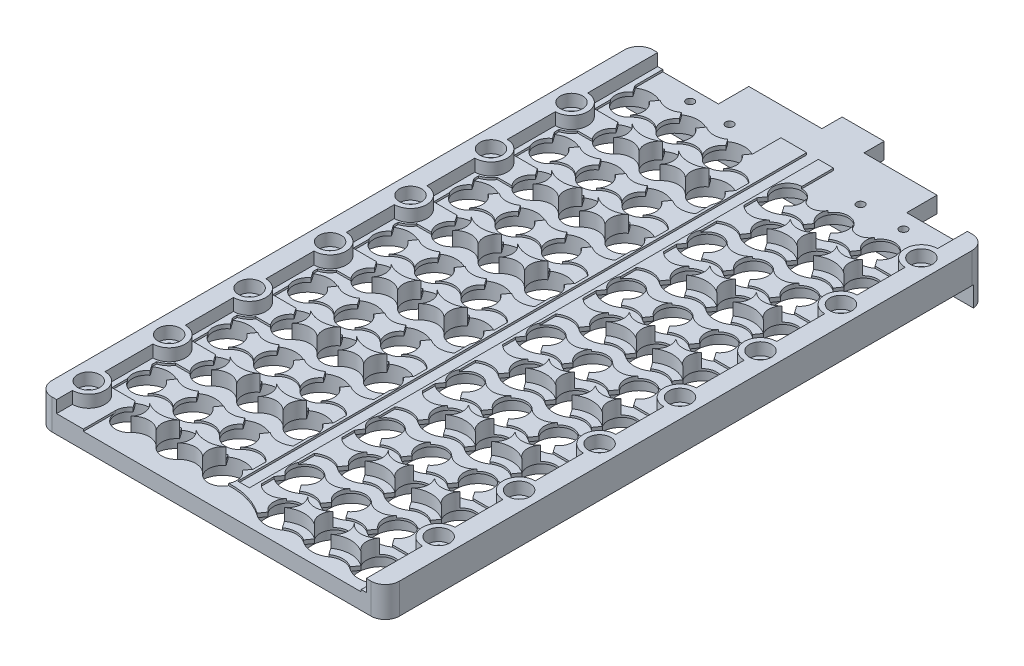
SolidWorks part; units mm, degrees
ref_plane "Front Plane" through (0, 0, 0) normal (0, 0, 1) x (1, 0, 0)
ref_plane "Top Plane" through (0, 0, 0) normal (0, 1, 0) x (1, 0, 0)
ref_plane "Right Plane" through (0, 0, 0) normal (1, 0, 0) x (0, 0, -1)
sketch "Sketch2" plane through (0, 0, 0) normal (0, 1, 0) x (1, 0, 0)
  line L1 (0, 0) -> (171.7, 0)
  line L2 (0, 0) -> (0, 290.6287)
  line L3 (0, 290.6287) -> (171.7, 290.6287)
  line L4 (171.7, 0) -> (171.7, 290.6287)
  dimension "D1" = 171.7
  dimension "D2" = 290.6287
extrude "Boss-Extrude6" add sketch "Sketch2" along normal blind 9
sketch "Sketch1" plane through (0, 0, 0) normal (0, 1, 0) x (1, 0, 0)
  line L1 (0, 0) -> (171.7029, 0)
  line L2 (0, 0) -> (0, 290.6287)
  line L3 (0, 290.6287) -> (171.7029, 290.6287)
  line L4 (171.7029, 0) -> (171.7029, 290.6287)
  line L5 (29.5647, 15.875) -> (18.0897, 35.7503) construction
  line L6 (18.0897, 35.7503) -> (18.0897, 15.875) construction
  line L7 (18.0897, 15.875) -> (29.5647, 15.875) construction
  line L8 (29.5647, 55.6256) -> (18.0897, 35.7503) construction
  line L9 (18.0897, 35.7503) -> (29.5647, 35.7503) construction
  line L10 (29.5647, 35.7503) -> (29.5647, 55.6256) construction
  line L11 (29.5647, 55.6256) -> (0, 55.6256) construction
  line L12 (0, 55.6256) -> (18.0897, 75.5008) construction
  line L13 (142.1382, 35.7503) -> (171.7029, 35.7503) construction
  line L14 (171.7029, 35.7503) -> (153.6132, 15.875) construction
  circle A1 centre (29.5647, 15.875) radius 10.875
  circle A2 centre (18.0897, 35.7503) radius 10.875
  circle A3 centre (41.0397, 35.7503) radius 10.875
  circle A4 centre (52.5147, 15.875) radius 10.875
  circle A5 centre (63.9897, 35.7503) radius 10.875
  circle A6 centre (75.4647, 15.875) radius 10.875
  circle A43 centre (96.2382, 35.7503) radius 10.875
  circle A44 centre (119.1882, 35.7503) radius 10.875
  circle A45 centre (142.1382, 35.7503) radius 10.875
  circle A46 centre (153.6132, 15.875) radius 10.875
  circle A47 centre (130.6632, 15.875) radius 10.875
  circle A48 centre (107.7132, 15.875) radius 10.875
  circle A49 centre (96.2382, 75.5008) radius 10.875
  circle A50 centre (119.1882, 75.5008) radius 10.875
  circle A51 centre (142.1382, 75.5008) radius 10.875
  circle A52 centre (153.6132, 55.6256) radius 10.875
  circle A53 centre (130.6632, 55.6256) radius 10.875
  circle A54 centre (107.7132, 55.6256) radius 10.875
  circle A55 centre (96.2382, 115.2514) radius 10.875
  circle A56 centre (119.1882, 115.2514) radius 10.875
  circle A57 centre (142.1382, 115.2514) radius 10.875
  circle A58 centre (153.6132, 95.3761) radius 10.875
  circle A59 centre (130.6632, 95.3761) radius 10.875
  circle A60 centre (107.7132, 95.3761) radius 10.875
  circle A61 centre (96.2382, 155.002) radius 10.875
  circle A62 centre (119.1882, 155.002) radius 10.875
  circle A63 centre (142.1382, 155.002) radius 10.875
  circle A64 centre (153.6132, 135.1267) radius 10.875
  circle A65 centre (130.6632, 135.1267) radius 10.875
  circle A66 centre (107.7132, 135.1267) radius 10.875
  circle A67 centre (96.2382, 194.7525) radius 10.875
  circle A68 centre (119.1882, 194.7525) radius 10.875
  circle A69 centre (142.1382, 194.7525) radius 10.875
  circle A70 centre (153.6132, 174.8773) radius 10.875
  circle A71 centre (130.6632, 174.8773) radius 10.875
  circle A72 centre (107.7132, 174.8773) radius 10.875
  circle A73 centre (96.2382, 234.5031) radius 10.875
  circle A74 centre (119.1882, 234.5031) radius 10.875
  circle A75 centre (142.1382, 234.5031) radius 10.875
  circle A76 centre (153.6132, 214.6278) radius 10.875
  circle A77 centre (130.6632, 214.6278) radius 10.875
  circle A78 centre (107.7132, 214.6278) radius 10.875
  circle A79 centre (96.2382, 274.2537) radius 10.875
  circle A80 centre (119.1882, 274.2537) radius 10.875
  circle A81 centre (142.1382, 274.2537) radius 10.875
  circle A82 centre (153.6132, 254.3784) radius 10.875
  circle A83 centre (130.6632, 254.3784) radius 10.875
  circle A84 centre (107.7132, 254.3784) radius 10.875
  circle A127 centre (18.0897, 75.5008) radius 10.875
  circle A128 centre (41.0397, 75.5008) radius 10.875
  circle A129 centre (63.9897, 75.5008) radius 10.875
  circle A130 centre (75.4647, 55.6256) radius 10.875
  circle A131 centre (52.5147, 55.6256) radius 10.875
  circle A132 centre (29.5647, 55.6256) radius 10.875
  circle A133 centre (18.0897, 115.2514) radius 10.875
  circle A134 centre (41.0397, 115.2514) radius 10.875
  circle A135 centre (63.9897, 115.2514) radius 10.875
  circle A136 centre (75.4647, 95.3761) radius 10.875
  circle A137 centre (52.5147, 95.3761) radius 10.875
  circle A138 centre (29.5647, 95.3761) radius 10.875
  circle A139 centre (18.0897, 155.002) radius 10.875
  circle A140 centre (41.0397, 155.002) radius 10.875
  circle A141 centre (63.9897, 155.002) radius 10.875
  circle A142 centre (75.4647, 135.1267) radius 10.875
  circle A143 centre (52.5147, 135.1267) radius 10.875
  circle A144 centre (29.5647, 135.1267) radius 10.875
  circle A145 centre (18.0897, 194.7525) radius 10.875
  circle A146 centre (41.0397, 194.7525) radius 10.875
  circle A147 centre (63.9897, 194.7525) radius 10.875
  circle A148 centre (75.4647, 174.8773) radius 10.875
  circle A149 centre (52.5147, 174.8773) radius 10.875
  circle A150 centre (29.5647, 174.8773) radius 10.875
  circle A151 centre (18.0897, 234.5031) radius 10.875
  circle A152 centre (41.0397, 234.5031) radius 10.875
  circle A153 centre (63.9897, 234.5031) radius 10.875
  circle A154 centre (75.4647, 214.6278) radius 10.875
  circle A155 centre (52.5147, 214.6278) radius 10.875
  circle A156 centre (29.5647, 214.6278) radius 10.875
  circle A157 centre (18.0897, 274.2537) radius 10.875
  circle A158 centre (41.0397, 274.2537) radius 10.875
  circle A159 centre (63.9897, 274.2537) radius 10.875
  circle A160 centre (75.4647, 254.3784) radius 10.875
  circle A161 centre (52.5147, 254.3784) radius 10.875
  circle A162 centre (29.5647, 254.3784) radius 10.875
  dimension "D1" = 21.75
  dimension "D2" = 15.875
  dimension "D3" = 22.95
  dimension "D5" = 60
  dimension "D8" = 22.95
  dimension "D9" = 22.95
  dimension "D10" = 60
  dimension "D13" = 28.75
  dimension "D4" = 16.375
  dimension "D16" = 26.875
  dimension "D14" = 26.875
  dimension "D6" = 3
  dimension "D7" = 1
  dimension "D11" = 2
  dimension "D12" = 7
extrude "Cut-Extrude1" cut sketch "Sketch1" along normal blind 7 contours A47 | A46 | A45 | A44 | A43 | A54 | A53 | A52 | A51 | A50 | A49 | A60 | A59 | A58 | A57 | A56 | A55 | A66 | A65 | A64 | A63 | A62 | A61 | A72 | A67 | A78 | A73 | A84 | A79 | A80 | A81 | A82 | A83 | A74 | A75 | A77 | A76 | A69 | A70 | A71 | A68 | A159 | A158 | A157 | A162 | A161 | A160 | A153 | A152 | A156 | A151 | A155 | A154 | A147 | A146 | A145 | A148 | A141 | A149 | A150 | A140 | A142 | A143 | A144 | A139 | A133 | A134 | A135 | A136 | A137 | A138 | A128 | A127 | A129 | A130 | A131 | A132 | A2 | A3 | A5 | A6 | A4 | A1 | A48 | A130 region at (29.5647, 0, -15.875) region at (18.0897, 0, -35.7503) region at (41.0397, 0, -35.7503) region at (52.5147, 0, -15.875) region at (63.9897, 0, -35.7503) region at (75.4647, 0, -15.875) region at (96.2382, 0, -35.7503) region at (119.1882, 0, -35.7503) region at (142.1382, 0, -35.7503) region at (153.6132, 0, -15.875) region at (130.6632, 0, -15.875) region at (96.2382, 0, -75.5008) region at (119.1882, 0, -75.5008) region at (142.1382, 0, -75.5008) region at (153.6132, 0, -55.6256) region at (130.6632, 0, -55.6256) region at (107.7132, 0, -55.6256) region at (96.2382, 0, -115.2514) region at (119.1882, 0, -115.2514) region at (142.1382, 0, -115.2514) region at (153.6132, 0, -95.3761) region at (130.6632, 0, -95.3761) region at (107.7132, 0, -95.3761) region at (96.2382, 0, -155.002) region at (119.1882, 0, -155.002) region at (142.1382, 0, -155.002) region at (153.6132, 0, -135.1267) region at (130.6632, 0, -135.1267) region at (107.7132, 0, -135.1267) region at (96.2382, 0, -194.7525) region at (119.1882, 0, -194.7525) region at (142.1382, 0, -194.7525) region at (153.6132, 0, -174.8773) region at (130.6632, 0, -174.8773) region at (107.7132, 0, -174.8773) region at (96.2382, 0, -234.5031) region at (119.1882, 0, -234.5031) region at (142.1382, 0, -234.5031) region at (153.6132, 0, -214.6278) region at (130.6632, 0, -214.6278) region at (107.7132, 0, -214.6278) region at (96.2382, 0, -274.2537) region at (119.1882, 0, -274.2537) region at (142.1382, 0, -274.2537) region at (153.6132, 0, -254.3784) region at (130.6632, 0, -254.3784) region at (107.7132, 0, -254.3784) region at (18.0897, 0, -75.5008) region at (41.0397, 0, -75.5008) region at (63.9897, 0, -75.5008) region at (75.4647, 0, -55.6256) region at (52.5147, 0, -55.6256) region at (29.5647, 0, -55.6256) region at (18.0897, 0, -115.2514) region at (41.0397, 0, -115.2514) region at (63.9897, 0, -115.2514) region at (75.4647, 0, -95.3761) region at (52.5147, 0, -95.3761) region at (29.5647, 0, -95.3761) region at (18.0897, 0, -155.002)
sketch "Sketch3" plane through (0, 0, 0) normal (0, -1, 0) x (1, 0, 0)
  line L0 (18.0897, -274.2537) -> (18.0897, -285.1287) construction
  line L1 (11.8521, -283.162) -> (18.0897, -274.2537) construction
  line L2 (18.0897, -274.2537) -> (24.3274, -283.162) construction
  line L3 (22.1048, -279.9877) -> (24.3274, -283.162)
  line L4 (14.0747, -279.9877) -> (11.8521, -283.162)
  line L5 (18.0897, -274.2537) -> (28.9647, -274.2537) construction
  line L6 (29.5647, -254.3784) -> (29.5647, -265.2534) construction
  line L7 (23.3271, -263.2867) -> (29.5647, -254.3784) construction
  line L8 (29.5647, -254.3784) -> (35.8024, -263.2867) construction
  line L9 (33.5798, -260.1125) -> (35.8024, -263.2867)
  line L10 (25.5497, -260.1125) -> (23.3271, -263.2867)
  line L11 (29.5647, -254.3784) -> (40.4397, -254.3784) construction
  line L12 (56.5298, -260.1125) -> (58.7524, -263.2867)
  line L13 (48.4997, -260.1125) -> (46.2771, -263.2867)
  line L14 (45.0548, -279.9877) -> (47.2774, -283.162)
  line L15 (37.0247, -279.9877) -> (34.8021, -283.162)
  line L16 (79.4798, -260.1125) -> (81.7024, -263.2867)
  line L17 (71.4497, -260.1125) -> (69.2271, -263.2867)
  line L18 (68.0048, -279.9877) -> (70.2274, -283.162)
  line L19 (59.9747, -279.9877) -> (57.7521, -283.162)
  line L178 (100.2532, -268.5196) -> (102.4758, -265.3454)
  line L181 (92.2231, -268.5196) -> (90.0005, -265.3454)
  line L182 (96.2382, -274.2537) -> (103.2382, -274.2537) construction
  line L183 (96.2382, -274.2537) -> (96.2382, -263.3787) construction
  line L184 (96.2382, -274.2537) -> (102.4758, -265.3454) construction
  line L186 (96.2382, -274.2537) -> (90.0005, -265.3454) construction
  line L187 (111.7282, -248.6443) -> (113.9508, -245.4701)
  line L188 (103.6981, -248.6443) -> (101.4755, -245.4701)
  line L189 (107.7132, -254.3784) -> (114.7132, -254.3784) construction
  line L190 (107.7132, -254.3784) -> (107.7132, -243.5034) construction
  line L191 (107.7132, -254.3784) -> (113.9508, -245.4701) construction
  line L192 (107.7132, -254.3784) -> (101.4755, -245.4701) construction
  line L193 (33.5798, -220.3619) -> (35.8024, -223.5361)
  line L194 (25.5497, -220.3619) -> (23.3271, -223.5361)
  line L195 (22.1048, -240.2372) -> (24.3274, -243.4114)
  line L196 (14.0747, -240.2372) -> (11.8521, -243.4114)
  line L197 (56.5298, -220.3619) -> (58.7524, -223.5361)
  line L198 (48.4997, -220.3619) -> (46.2771, -223.5361)
  line L199 (45.0548, -240.2372) -> (47.2774, -243.4114)
  line L200 (37.0247, -240.2372) -> (34.8021, -243.4114)
  line L201 (79.4798, -220.3619) -> (81.7024, -223.5361)
  line L202 (71.4497, -220.3619) -> (69.2271, -223.5361)
  line L203 (68.0048, -240.2372) -> (70.2274, -243.4114)
  line L204 (59.9747, -240.2372) -> (57.7521, -243.4114)
  line L205 (33.5798, -180.6113) -> (35.8024, -183.7855)
  line L206 (25.5497, -180.6113) -> (23.3271, -183.7855)
  line L207 (22.1048, -200.4866) -> (24.3274, -203.6608)
  line L208 (14.0747, -200.4866) -> (11.8521, -203.6608)
  line L209 (56.5298, -180.6113) -> (58.7524, -183.7855)
  line L210 (48.4997, -180.6113) -> (46.2771, -183.7855)
  line L211 (45.0548, -200.4866) -> (47.2774, -203.6608)
  line L212 (37.0247, -200.4866) -> (34.8021, -203.6608)
  line L213 (79.4798, -180.6113) -> (81.7024, -183.7855)
  line L214 (71.4497, -180.6113) -> (69.2271, -183.7855)
  line L215 (68.0048, -200.4866) -> (70.2274, -203.6608)
  line L216 (59.9747, -200.4866) -> (57.7521, -203.6608)
  line L217 (33.5798, -140.8608) -> (35.8024, -144.035)
  line L218 (25.5497, -140.8608) -> (23.3271, -144.035)
  line L219 (22.1048, -160.736) -> (24.3274, -163.9103)
  line L220 (14.0747, -160.736) -> (11.8521, -163.9103)
  line L221 (56.5298, -140.8608) -> (58.7524, -144.035)
  line L222 (48.4997, -140.8608) -> (46.2771, -144.035)
  line L223 (45.0548, -160.736) -> (47.2774, -163.9103)
  line L224 (37.0247, -160.736) -> (34.8021, -163.9103)
  line L225 (79.4798, -140.8608) -> (81.7024, -144.035)
  line L226 (71.4497, -140.8608) -> (69.2271, -144.035)
  line L227 (68.0048, -160.736) -> (70.2274, -163.9103)
  line L228 (59.9747, -160.736) -> (57.7521, -163.9103)
  line L229 (33.5798, -101.1102) -> (35.8024, -104.2844)
  line L230 (25.5497, -101.1102) -> (23.3271, -104.2844)
  line L231 (22.1048, -120.9855) -> (24.3274, -124.1597)
  line L232 (14.0747, -120.9855) -> (11.8521, -124.1597)
  line L233 (56.5298, -101.1102) -> (58.7524, -104.2844)
  line L234 (48.4997, -101.1102) -> (46.2771, -104.2844)
  line L235 (45.0548, -120.9855) -> (47.2774, -124.1597)
  line L236 (37.0247, -120.9855) -> (34.8021, -124.1597)
  line L237 (79.4798, -101.1102) -> (81.7024, -104.2844)
  line L238 (71.4497, -101.1102) -> (69.2271, -104.2844)
  line L239 (68.0048, -120.9855) -> (70.2274, -124.1597)
  line L240 (59.9747, -120.9855) -> (57.7521, -124.1597)
  line L241 (33.5798, -61.3596) -> (35.8024, -64.5338)
  line L242 (25.5497, -61.3596) -> (23.3271, -64.5338)
  line L243 (22.1048, -81.2349) -> (24.3274, -84.4091)
  line L244 (14.0747, -81.2349) -> (11.8521, -84.4091)
  line L245 (56.5298, -61.3596) -> (58.7524, -64.5338)
  line L246 (48.4997, -61.3596) -> (46.2771, -64.5338)
  line L247 (45.0548, -81.2349) -> (47.2774, -84.4091)
  line L248 (37.0247, -81.2349) -> (34.8021, -84.4091)
  line L249 (79.4798, -61.3596) -> (81.7024, -64.5338)
  line L250 (71.4497, -61.3596) -> (69.2271, -64.5338)
  line L251 (68.0048, -81.2349) -> (70.2274, -84.4091)
  line L252 (59.9747, -81.2349) -> (57.7521, -84.4091)
  line L253 (33.5798, -21.6091) -> (35.8024, -24.7833)
  line L254 (25.5497, -21.6091) -> (23.3271, -24.7833)
  line L255 (22.1048, -41.4843) -> (24.3274, -44.6586)
  line L256 (14.0747, -41.4843) -> (11.8521, -44.6586)
  line L257 (56.5298, -21.6091) -> (58.7524, -24.7833)
  line L258 (48.4997, -21.6091) -> (46.2771, -24.7833)
  line L259 (45.0548, -41.4843) -> (47.2774, -44.6586)
  line L260 (37.0247, -41.4843) -> (34.8021, -44.6586)
  line L261 (79.4798, -21.6091) -> (81.7024, -24.7833)
  line L262 (71.4497, -21.6091) -> (69.2271, -24.7833)
  line L263 (68.0048, -41.4843) -> (70.2274, -44.6586)
  line L264 (59.9747, -41.4843) -> (57.7521, -44.6586)
  line L265 (123.2032, -268.5196) -> (125.4258, -265.3454)
  line L266 (115.1731, -268.5196) -> (112.9505, -265.3454)
  line L267 (134.6782, -248.6443) -> (136.9008, -245.4701)
  line L268 (126.6481, -248.6443) -> (124.4255, -245.4701)
  line L269 (146.1532, -268.5196) -> (148.3758, -265.3454)
  line L270 (138.1231, -268.5196) -> (135.9005, -265.3454)
  line L271 (157.6282, -248.6443) -> (159.8508, -245.4701)
  line L272 (149.5981, -248.6443) -> (147.3755, -245.4701)
  line L273 (123.2032, -228.769) -> (125.4258, -225.5948)
  line L274 (115.1731, -228.769) -> (112.9505, -225.5948)
  line L275 (134.6782, -208.8938) -> (136.9008, -205.7196)
  line L276 (126.6481, -208.8938) -> (124.4255, -205.7196)
  line L277 (146.1532, -228.769) -> (148.3758, -225.5948)
  line L278 (138.1231, -228.769) -> (135.9005, -225.5948)
  line L279 (157.6282, -208.8938) -> (159.8508, -205.7196)
  line L280 (149.5981, -208.8938) -> (147.3755, -205.7196)
  line L281 (123.2032, -189.0185) -> (125.4258, -185.8443)
  line L282 (115.1731, -189.0185) -> (112.9505, -185.8443)
  line L283 (134.6782, -169.1432) -> (136.9008, -165.969)
  line L284 (126.6481, -169.1432) -> (124.4255, -165.969)
  line L285 (146.1532, -189.0185) -> (148.3758, -185.8443)
  line L286 (138.1231, -189.0185) -> (135.9005, -185.8443)
  line L287 (157.6282, -169.1432) -> (159.8508, -165.969)
  line L288 (149.5981, -169.1432) -> (147.3755, -165.969)
  line L289 (123.2032, -149.2679) -> (125.4258, -146.0937)
  line L290 (115.1731, -149.2679) -> (112.9505, -146.0937)
  line L291 (134.6782, -129.3926) -> (136.9008, -126.2184)
  line L292 (126.6481, -129.3926) -> (124.4255, -126.2184)
  line L293 (146.1532, -149.2679) -> (148.3758, -146.0937)
  line L294 (138.1231, -149.2679) -> (135.9005, -146.0937)
  line L295 (157.6282, -129.3926) -> (159.8508, -126.2184)
  line L296 (149.5981, -129.3926) -> (147.3755, -126.2184)
  line L297 (123.2032, -109.5174) -> (125.4258, -106.3431)
  line L298 (115.1731, -109.5174) -> (112.9505, -106.3431)
  line L299 (134.6782, -89.6421) -> (136.9008, -86.4679)
  line L300 (126.6481, -89.6421) -> (124.4255, -86.4679)
  line L301 (146.1532, -109.5174) -> (148.3758, -106.3431)
  line L302 (138.1231, -109.5174) -> (135.9005, -106.3431)
  line L303 (157.6282, -89.6421) -> (159.8508, -86.4679)
  line L304 (149.5981, -89.6421) -> (147.3755, -86.4679)
  line L305 (123.2032, -69.7668) -> (125.4258, -66.5926)
  line L306 (115.1731, -69.7668) -> (112.9505, -66.5926)
  line L307 (134.6782, -49.8915) -> (136.9008, -46.7173)
  line L308 (126.6481, -49.8915) -> (124.4255, -46.7173)
  line L309 (146.1532, -69.7668) -> (148.3758, -66.5926)
  line L310 (138.1231, -69.7668) -> (135.9005, -66.5926)
  line L311 (157.6282, -49.8915) -> (159.8508, -46.7173)
  line L312 (149.5981, -49.8915) -> (147.3755, -46.7173)
  line L313 (123.2032, -30.0162) -> (125.4258, -26.842)
  line L314 (115.1731, -30.0162) -> (112.9505, -26.842)
  line L315 (134.6782, -10.1409) -> (136.9008, -6.9667)
  line L316 (126.6481, -10.1409) -> (124.4255, -6.9667)
  line L317 (146.1532, -30.0162) -> (148.3758, -26.842)
  line L318 (138.1231, -30.0162) -> (135.9005, -26.842)
  line L319 (157.6282, -10.1409) -> (159.8508, -6.9667)
  line L320 (149.5981, -10.1409) -> (147.3755, -6.9667)
  line L321 (100.2532, -228.769) -> (102.4758, -225.5948)
  line L322 (92.2231, -228.769) -> (90.0005, -225.5948)
  line L323 (111.7282, -208.8938) -> (113.9508, -205.7196)
  line L324 (103.6981, -208.8938) -> (101.4755, -205.7196)
  line L325 (100.2532, -189.0185) -> (102.4758, -185.8443)
  line L326 (92.2231, -189.0185) -> (90.0005, -185.8443)
  line L327 (111.7282, -169.1432) -> (113.9508, -165.969)
  line L328 (103.6981, -169.1432) -> (101.4755, -165.969)
  line L329 (100.2532, -149.2679) -> (102.4758, -146.0937)
  line L330 (92.2231, -149.2679) -> (90.0005, -146.0937)
  line L331 (111.7282, -129.3926) -> (113.9508, -126.2184)
  line L332 (103.6981, -129.3926) -> (101.4755, -126.2184)
  line L333 (100.2532, -109.5174) -> (102.4758, -106.3431)
  line L334 (92.2231, -109.5174) -> (90.0005, -106.3431)
  line L335 (111.7282, -89.6421) -> (113.9508, -86.4679)
  line L336 (103.6981, -89.6421) -> (101.4755, -86.4679)
  line L337 (100.2532, -69.7668) -> (102.4758, -66.5926)
  line L338 (92.2231, -69.7668) -> (90.0005, -66.5926)
  line L339 (111.7282, -49.8915) -> (113.9508, -46.7173)
  line L340 (103.6981, -49.8915) -> (101.4755, -46.7173)
  line L341 (100.2532, -30.0162) -> (102.4758, -26.842)
  line L342 (92.2231, -30.0162) -> (90.0005, -26.842)
  line L343 (111.7282, -10.1409) -> (113.9508, -6.9667)
  line L344 (103.6981, -10.1409) -> (101.4755, -6.9667)
  arc A0 (14.0747, -279.9877) -> (22.1048, -279.9877) centre (18.0897, -274.2537) cw
  arc A1 (11.8521, -283.162) -> (24.3274, -283.162) centre (18.0897, -274.2537) ccw
  circle A2 centre (18.0897, -274.2537) radius 10.875 construction
  circle A3 centre (18.0897, -274.2537) radius 10.875 construction
  arc A4 (25.5497, -260.1125) -> (33.5798, -260.1125) centre (29.5647, -254.3784) cw
  arc A5 (23.3271, -263.2867) -> (35.8024, -263.2867) centre (29.5647, -254.3784) ccw
  circle A7 centre (29.5647, -254.3784) radius 10.875 construction
  circle A8 centre (29.5647, -254.3784) radius 10.875 construction
  arc A9 (46.2771, -263.2867) -> (58.7524, -263.2867) centre (52.5147, -254.3784) ccw
  arc A10 (48.4997, -260.1125) -> (56.5298, -260.1125) centre (52.5147, -254.3784) cw
  arc A11 (34.8021, -283.162) -> (47.2774, -283.162) centre (41.0397, -274.2537) ccw
  arc A12 (37.0247, -279.9877) -> (45.0548, -279.9877) centre (41.0397, -274.2537) cw
  arc A13 (69.2271, -263.2867) -> (81.7024, -263.2867) centre (75.4647, -254.3784) ccw
  arc A14 (71.4497, -260.1125) -> (79.4798, -260.1125) centre (75.4647, -254.3784) cw
  arc A15 (57.7521, -283.162) -> (70.2274, -283.162) centre (63.9897, -274.2537) ccw
  arc A16 (59.9747, -279.9877) -> (68.0048, -279.9877) centre (63.9897, -274.2537) cw
  circle A18 centre (41.0397, -274.2537) radius 10.875 construction
  arc A177 (101.4755, -245.4701) -> (113.9508, -245.4701) centre (107.7132, -254.3784) cw
  arc A178 (103.6981, -248.6443) -> (111.7282, -248.6443) centre (107.7132, -254.3784) ccw
  arc A181 (90.0005, -265.3454) -> (102.4758, -265.3454) centre (96.2382, -274.2537) cw
  circle A182 centre (107.7132, -254.3784) radius 10.875 construction
  arc A183 (23.3271, -223.5361) -> (35.8024, -223.5361) centre (29.5647, -214.6278) ccw
  arc A184 (92.2231, -268.5196) -> (100.2532, -268.5196) centre (96.2382, -274.2537) ccw
  circle A185 centre (96.2382, -274.2537) radius 10.875 construction
  arc A186 (25.5497, -220.3619) -> (33.5798, -220.3619) centre (29.5647, -214.6278) cw
  arc A187 (11.8521, -243.4114) -> (24.3274, -243.4114) centre (18.0897, -234.5031) ccw
  arc A188 (14.0747, -240.2372) -> (22.1048, -240.2372) centre (18.0897, -234.5031) cw
  arc A189 (46.2771, -223.5361) -> (58.7524, -223.5361) centre (52.5147, -214.6278) ccw
  arc A190 (48.4997, -220.3619) -> (56.5298, -220.3619) centre (52.5147, -214.6278) cw
  arc A191 (34.8021, -243.4114) -> (47.2774, -243.4114) centre (41.0397, -234.5031) ccw
  arc A192 (37.0247, -240.2372) -> (45.0548, -240.2372) centre (41.0397, -234.5031) cw
  arc A193 (69.2271, -223.5361) -> (81.7024, -223.5361) centre (75.4647, -214.6278) ccw
  arc A194 (71.4497, -220.3619) -> (79.4798, -220.3619) centre (75.4647, -214.6278) cw
  arc A195 (57.7521, -243.4114) -> (70.2274, -243.4114) centre (63.9897, -234.5031) ccw
  arc A196 (59.9747, -240.2372) -> (68.0048, -240.2372) centre (63.9897, -234.5031) cw
  arc A197 (23.3271, -183.7855) -> (35.8024, -183.7855) centre (29.5647, -174.8773) ccw
  arc A198 (25.5497, -180.6113) -> (33.5798, -180.6113) centre (29.5647, -174.8773) cw
  arc A199 (11.8521, -203.6608) -> (24.3274, -203.6608) centre (18.0897, -194.7525) ccw
  arc A200 (14.0747, -200.4866) -> (22.1048, -200.4866) centre (18.0897, -194.7525) cw
  arc A201 (46.2771, -183.7855) -> (58.7524, -183.7855) centre (52.5147, -174.8773) ccw
  arc A202 (48.4997, -180.6113) -> (56.5298, -180.6113) centre (52.5147, -174.8773) cw
  arc A203 (34.8021, -203.6608) -> (47.2774, -203.6608) centre (41.0397, -194.7525) ccw
  arc A204 (37.0247, -200.4866) -> (45.0548, -200.4866) centre (41.0397, -194.7525) cw
  arc A205 (69.2271, -183.7855) -> (81.7024, -183.7855) centre (75.4647, -174.8773) ccw
  arc A206 (71.4497, -180.6113) -> (79.4798, -180.6113) centre (75.4647, -174.8773) cw
  arc A207 (57.7521, -203.6608) -> (70.2274, -203.6608) centre (63.9897, -194.7525) ccw
  arc A208 (59.9747, -200.4866) -> (68.0048, -200.4866) centre (63.9897, -194.7525) cw
  arc A209 (23.3271, -144.035) -> (35.8024, -144.035) centre (29.5647, -135.1267) ccw
  arc A210 (25.5497, -140.8608) -> (33.5798, -140.8608) centre (29.5647, -135.1267) cw
  arc A211 (11.8521, -163.9103) -> (24.3274, -163.9103) centre (18.0897, -155.002) ccw
  arc A212 (14.0747, -160.736) -> (22.1048, -160.736) centre (18.0897, -155.002) cw
  arc A213 (46.2771, -144.035) -> (58.7524, -144.035) centre (52.5147, -135.1267) ccw
  arc A214 (48.4997, -140.8608) -> (56.5298, -140.8608) centre (52.5147, -135.1267) cw
  arc A215 (34.8021, -163.9103) -> (47.2774, -163.9103) centre (41.0397, -155.002) ccw
  arc A216 (37.0247, -160.736) -> (45.0548, -160.736) centre (41.0397, -155.002) cw
  arc A217 (69.2271, -144.035) -> (81.7024, -144.035) centre (75.4647, -135.1267) ccw
  arc A218 (71.4497, -140.8608) -> (79.4798, -140.8608) centre (75.4647, -135.1267) cw
  arc A219 (57.7521, -163.9103) -> (70.2274, -163.9103) centre (63.9897, -155.002) ccw
  arc A220 (59.9747, -160.736) -> (68.0048, -160.736) centre (63.9897, -155.002) cw
  arc A221 (23.3271, -104.2844) -> (35.8024, -104.2844) centre (29.5647, -95.3761) ccw
  arc A222 (25.5497, -101.1102) -> (33.5798, -101.1102) centre (29.5647, -95.3761) cw
  arc A223 (11.8521, -124.1597) -> (24.3274, -124.1597) centre (18.0897, -115.2514) ccw
  arc A224 (14.0747, -120.9855) -> (22.1048, -120.9855) centre (18.0897, -115.2514) cw
  arc A225 (46.2771, -104.2844) -> (58.7524, -104.2844) centre (52.5147, -95.3761) ccw
  arc A226 (48.4997, -101.1102) -> (56.5298, -101.1102) centre (52.5147, -95.3761) cw
  arc A227 (34.8021, -124.1597) -> (47.2774, -124.1597) centre (41.0397, -115.2514) ccw
  arc A228 (37.0247, -120.9855) -> (45.0548, -120.9855) centre (41.0397, -115.2514) cw
  arc A229 (69.2271, -104.2844) -> (81.7024, -104.2844) centre (75.4647, -95.3761) ccw
  arc A230 (71.4497, -101.1102) -> (79.4798, -101.1102) centre (75.4647, -95.3761) cw
  arc A231 (57.7521, -124.1597) -> (70.2274, -124.1597) centre (63.9897, -115.2514) ccw
  arc A232 (59.9747, -120.9855) -> (68.0048, -120.9855) centre (63.9897, -115.2514) cw
  arc A233 (23.3271, -64.5338) -> (35.8024, -64.5338) centre (29.5647, -55.6256) ccw
  arc A234 (25.5497, -61.3596) -> (33.5798, -61.3596) centre (29.5647, -55.6256) cw
  arc A235 (11.8521, -84.4091) -> (24.3274, -84.4091) centre (18.0897, -75.5008) ccw
  arc A236 (14.0747, -81.2349) -> (22.1048, -81.2349) centre (18.0897, -75.5008) cw
  arc A237 (46.2771, -64.5338) -> (58.7524, -64.5338) centre (52.5147, -55.6256) ccw
  arc A238 (48.4997, -61.3596) -> (56.5298, -61.3596) centre (52.5147, -55.6256) cw
  arc A239 (34.8021, -84.4091) -> (47.2774, -84.4091) centre (41.0397, -75.5008) ccw
  arc A240 (37.0247, -81.2349) -> (45.0548, -81.2349) centre (41.0397, -75.5008) cw
  arc A241 (69.2271, -64.5338) -> (81.7024, -64.5338) centre (75.4647, -55.6256) ccw
  arc A242 (71.4497, -61.3596) -> (79.4798, -61.3596) centre (75.4647, -55.6256) cw
  arc A243 (57.7521, -84.4091) -> (70.2274, -84.4091) centre (63.9897, -75.5008) ccw
  arc A244 (59.9747, -81.2349) -> (68.0048, -81.2349) centre (63.9897, -75.5008) cw
  arc A245 (23.3271, -24.7833) -> (35.8024, -24.7833) centre (29.5647, -15.875) ccw
  arc A246 (25.5497, -21.6091) -> (33.5798, -21.6091) centre (29.5647, -15.875) cw
  arc A247 (11.8521, -44.6586) -> (24.3274, -44.6586) centre (18.0897, -35.7503) ccw
  arc A248 (14.0747, -41.4843) -> (22.1048, -41.4843) centre (18.0897, -35.7503) cw
  arc A249 (46.2771, -24.7833) -> (58.7524, -24.7833) centre (52.5147, -15.875) ccw
  arc A250 (48.4997, -21.6091) -> (56.5298, -21.6091) centre (52.5147, -15.875) cw
  arc A251 (34.8021, -44.6586) -> (47.2774, -44.6586) centre (41.0397, -35.7503) ccw
  arc A252 (37.0247, -41.4843) -> (45.0548, -41.4843) centre (41.0397, -35.7503) cw
  arc A253 (69.2271, -24.7833) -> (81.7024, -24.7833) centre (75.4647, -15.875) ccw
  arc A254 (71.4497, -21.6091) -> (79.4798, -21.6091) centre (75.4647, -15.875) cw
  arc A255 (57.7521, -44.6586) -> (70.2274, -44.6586) centre (63.9897, -35.7503) ccw
  arc A256 (59.9747, -41.4843) -> (68.0048, -41.4843) centre (63.9897, -35.7503) cw
  arc A257 (112.9505, -265.3454) -> (125.4258, -265.3454) centre (119.1882, -274.2537) cw
  arc A258 (115.1731, -268.5196) -> (123.2032, -268.5196) centre (119.1882, -274.2537) ccw
  arc A259 (124.4255, -245.4701) -> (136.9008, -245.4701) centre (130.6632, -254.3784) cw
  arc A260 (126.6481, -248.6443) -> (134.6782, -248.6443) centre (130.6632, -254.3784) ccw
  arc A261 (135.9005, -265.3454) -> (148.3758, -265.3454) centre (142.1382, -274.2537) cw
  arc A262 (138.1231, -268.5196) -> (146.1532, -268.5196) centre (142.1382, -274.2537) ccw
  arc A263 (147.3755, -245.4701) -> (159.8508, -245.4701) centre (153.6132, -254.3784) cw
  arc A264 (149.5981, -248.6443) -> (157.6282, -248.6443) centre (153.6132, -254.3784) ccw
  arc A265 (112.9505, -225.5948) -> (125.4258, -225.5948) centre (119.1882, -234.5031) cw
  arc A266 (115.1731, -228.769) -> (123.2032, -228.769) centre (119.1882, -234.5031) ccw
  arc A267 (124.4255, -205.7196) -> (136.9008, -205.7196) centre (130.6632, -214.6278) cw
  arc A268 (126.6481, -208.8938) -> (134.6782, -208.8938) centre (130.6632, -214.6278) ccw
  arc A269 (135.9005, -225.5948) -> (148.3758, -225.5948) centre (142.1382, -234.5031) cw
  arc A270 (138.1231, -228.769) -> (146.1532, -228.769) centre (142.1382, -234.5031) ccw
  arc A271 (147.3755, -205.7196) -> (159.8508, -205.7196) centre (153.6132, -214.6278) cw
  arc A272 (149.5981, -208.8938) -> (157.6282, -208.8938) centre (153.6132, -214.6278) ccw
  arc A273 (112.9505, -185.8443) -> (125.4258, -185.8443) centre (119.1882, -194.7525) cw
  arc A274 (115.1731, -189.0185) -> (123.2032, -189.0185) centre (119.1882, -194.7525) ccw
  arc A275 (124.4255, -165.969) -> (136.9008, -165.969) centre (130.6632, -174.8773) cw
  arc A276 (126.6481, -169.1432) -> (134.6782, -169.1432) centre (130.6632, -174.8773) ccw
  arc A277 (135.9005, -185.8443) -> (148.3758, -185.8443) centre (142.1382, -194.7525) cw
  arc A278 (138.1231, -189.0185) -> (146.1532, -189.0185) centre (142.1382, -194.7525) ccw
  arc A279 (147.3755, -165.969) -> (159.8508, -165.969) centre (153.6132, -174.8773) cw
  arc A280 (149.5981, -169.1432) -> (157.6282, -169.1432) centre (153.6132, -174.8773) ccw
  arc A281 (112.9505, -146.0937) -> (125.4258, -146.0937) centre (119.1882, -155.002) cw
  arc A282 (115.1731, -149.2679) -> (123.2032, -149.2679) centre (119.1882, -155.002) ccw
  arc A283 (124.4255, -126.2184) -> (136.9008, -126.2184) centre (130.6632, -135.1267) cw
  arc A284 (126.6481, -129.3926) -> (134.6782, -129.3926) centre (130.6632, -135.1267) ccw
  arc A285 (135.9005, -146.0937) -> (148.3758, -146.0937) centre (142.1382, -155.002) cw
  arc A286 (138.1231, -149.2679) -> (146.1532, -149.2679) centre (142.1382, -155.002) ccw
  arc A287 (147.3755, -126.2184) -> (159.8508, -126.2184) centre (153.6132, -135.1267) cw
  arc A288 (149.5981, -129.3926) -> (157.6282, -129.3926) centre (153.6132, -135.1267) ccw
  arc A289 (112.9505, -106.3431) -> (125.4258, -106.3431) centre (119.1882, -115.2514) cw
  arc A290 (115.1731, -109.5174) -> (123.2032, -109.5174) centre (119.1882, -115.2514) ccw
  arc A291 (124.4255, -86.4679) -> (136.9008, -86.4679) centre (130.6632, -95.3761) cw
  arc A292 (126.6481, -89.6421) -> (134.6782, -89.6421) centre (130.6632, -95.3761) ccw
  arc A293 (135.9005, -106.3431) -> (148.3758, -106.3431) centre (142.1382, -115.2514) cw
  arc A294 (138.1231, -109.5174) -> (146.1532, -109.5174) centre (142.1382, -115.2514) ccw
  arc A295 (147.3755, -86.4679) -> (159.8508, -86.4679) centre (153.6132, -95.3761) cw
  arc A296 (149.5981, -89.6421) -> (157.6282, -89.6421) centre (153.6132, -95.3761) ccw
  arc A297 (112.9505, -66.5926) -> (125.4258, -66.5926) centre (119.1882, -75.5008) cw
  arc A298 (115.1731, -69.7668) -> (123.2032, -69.7668) centre (119.1882, -75.5008) ccw
  arc A299 (124.4255, -46.7173) -> (136.9008, -46.7173) centre (130.6632, -55.6256) cw
  arc A300 (126.6481, -49.8915) -> (134.6782, -49.8915) centre (130.6632, -55.6256) ccw
  arc A301 (135.9005, -66.5926) -> (148.3758, -66.5926) centre (142.1382, -75.5008) cw
  arc A302 (138.1231, -69.7668) -> (146.1532, -69.7668) centre (142.1382, -75.5008) ccw
  arc A303 (147.3755, -46.7173) -> (159.8508, -46.7173) centre (153.6132, -55.6256) cw
  arc A304 (149.5981, -49.8915) -> (157.6282, -49.8915) centre (153.6132, -55.6256) ccw
  arc A305 (112.9505, -26.842) -> (125.4258, -26.842) centre (119.1882, -35.7503) cw
  arc A306 (115.1731, -30.0162) -> (123.2032, -30.0162) centre (119.1882, -35.7503) ccw
  arc A307 (124.4255, -6.9667) -> (136.9008, -6.9667) centre (130.6632, -15.875) cw
  arc A308 (126.6481, -10.1409) -> (134.6782, -10.1409) centre (130.6632, -15.875) ccw
  arc A309 (135.9005, -26.842) -> (148.3758, -26.842) centre (142.1382, -35.7503) cw
  arc A310 (138.1231, -30.0162) -> (146.1532, -30.0162) centre (142.1382, -35.7503) ccw
  arc A311 (147.3755, -6.9667) -> (159.8508, -6.9667) centre (153.6132, -15.875) cw
  arc A312 (149.5981, -10.1409) -> (157.6282, -10.1409) centre (153.6132, -15.875) ccw
  arc A313 (90.0005, -225.5948) -> (102.4758, -225.5948) centre (96.2382, -234.5031) cw
  arc A314 (92.2231, -228.769) -> (100.2532, -228.769) centre (96.2382, -234.5031) ccw
  arc A315 (101.4755, -205.7196) -> (113.9508, -205.7196) centre (107.7132, -214.6278) cw
  arc A316 (103.6981, -208.8938) -> (111.7282, -208.8938) centre (107.7132, -214.6278) ccw
  arc A317 (90.0005, -185.8443) -> (102.4758, -185.8443) centre (96.2382, -194.7525) cw
  arc A318 (92.2231, -189.0185) -> (100.2532, -189.0185) centre (96.2382, -194.7525) ccw
  arc A319 (101.4755, -165.969) -> (113.9508, -165.969) centre (107.7132, -174.8773) cw
  arc A320 (103.6981, -169.1432) -> (111.7282, -169.1432) centre (107.7132, -174.8773) ccw
  arc A321 (90.0005, -146.0937) -> (102.4758, -146.0937) centre (96.2382, -155.002) cw
  arc A322 (92.2231, -149.2679) -> (100.2532, -149.2679) centre (96.2382, -155.002) ccw
  arc A323 (101.4755, -126.2184) -> (113.9508, -126.2184) centre (107.7132, -135.1267) cw
  arc A324 (103.6981, -129.3926) -> (111.7282, -129.3926) centre (107.7132, -135.1267) ccw
  arc A325 (90.0005, -106.3431) -> (102.4758, -106.3431) centre (96.2382, -115.2514) cw
  arc A326 (92.2231, -109.5174) -> (100.2532, -109.5174) centre (96.2382, -115.2514) ccw
  arc A327 (101.4755, -86.4679) -> (113.9508, -86.4679) centre (107.7132, -95.3761) cw
  arc A328 (103.6981, -89.6421) -> (111.7282, -89.6421) centre (107.7132, -95.3761) ccw
  arc A329 (90.0005, -66.5926) -> (102.4758, -66.5926) centre (96.2382, -75.5008) cw
  arc A330 (92.2231, -69.7668) -> (100.2532, -69.7668) centre (96.2382, -75.5008) ccw
  arc A331 (101.4755, -46.7173) -> (113.9508, -46.7173) centre (107.7132, -55.6256) cw
  arc A332 (103.6981, -49.8915) -> (111.7282, -49.8915) centre (107.7132, -55.6256) ccw
  arc A333 (90.0005, -26.842) -> (102.4758, -26.842) centre (96.2382, -35.7503) cw
  arc A334 (92.2231, -30.0162) -> (100.2532, -30.0162) centre (96.2382, -35.7503) ccw
  arc A335 (101.4755, -6.9667) -> (113.9508, -6.9667) centre (107.7132, -15.875) cw
  arc A336 (103.6981, -10.1409) -> (111.7282, -10.1409) centre (107.7132, -15.875) ccw
  circle A337 centre (63.9897, -234.5031) radius 10.875 construction
  dimension "D1" = 7
  dimension "D4" = 7
  dimension "D9" = 7
  dimension "D12" = 7
  dimension "D2" = 70
  dimension "D3" = 125
  dimension "D5" = 70
  dimension "D6" = 125
  dimension "D10" = 70
  dimension "D11" = 125
  dimension "D13" = 70
  dimension "D14" = 125
  dimension "D7" = 3
  dimension "D15" = 7
extrude "Cut-Extrude2" cut sketch "Sketch3" against normal up to surface (9 mm away) up to face at (85.85, 9, -145.3143)
sketch "Sketch5" plane through (0, 9, 0) normal (0, 1, 0) x (1, 0, 0)
  line L0 (18.6897, 254.3784) -> (9.3449, 254.3784) construction
  line L1 (9.3449, 254.3784) -> (0, 254.3784) construction
  line L2 (18.0897, 234.5031) -> (9.3449, 254.3784) construction
  line L3 (9.3449, 254.3784) -> (18.0897, 274.2537) construction
  line L5 (0, 290.6287) -> (0, 0) construction
  line L6 (162.3566, 35.7503) -> (171.7, 35.7503) construction
  line L7 (153.6132, 15.875) -> (162.3566, 35.7503) construction
  line L8 (162.3566, 35.7503) -> (153.6132, 55.6256) construction
  line L9 (171.7, 0) -> (171.7, 290.6287) construction
  line L10 (162.3566, 35.7503) -> (153.0132, 35.7503) construction
  line L11 (142.1382, 75.5008) -> (171.7, 75.5008) construction
  line L12 (29.5647, 214.6278) -> (0, 214.6278) construction
  circle A1 centre (9.3449, 254.3784) radius 3.3
  circle A2 centre (29.5647, 254.3784) radius 10.875 construction
  arc A3 (23.3271, 263.2867) -> (35.8024, 263.2867) centre (29.5647, 254.3784) ccw construction
  circle A4 centre (162.3566, 35.7503) radius 3.3
  arc A5 (148.3758, 26.842) -> (135.9005, 26.842) centre (142.1382, 35.7503) ccw construction
  circle A6 centre (142.1382, 35.7503) radius 10.875 construction
  circle A7 centre (162.3566, 75.5008) radius 3.3
  circle A8 centre (162.3566, 115.2514) radius 3.3
  circle A9 centre (162.3566, 155.002) radius 3.3
  circle A10 centre (162.3566, 194.7525) radius 3.3
  circle A11 centre (162.3566, 234.5031) radius 3.3
  circle A12 centre (162.3566, 274.2537) radius 3.3
  circle A15 centre (9.3449, 214.6278) radius 3.3
  circle A16 centre (9.3449, 174.8773) radius 3.3
  circle A17 centre (9.3449, 135.1267) radius 3.3
  circle A18 centre (9.3449, 95.3761) radius 3.3
  circle A19 centre (9.3449, 55.6256) radius 3.3
  circle A20 centre (9.3449, 15.875) radius 3.3
  dimension "D4" = 7
  dimension "D1" = 6.6
  dimension "D2" = 6.6
  dimension "D3" = 7
extrude "Cut-Extrude3" cut sketch "Sketch5" against normal up to surface (9 mm away) up to face at (96.2382, 0, -64.6258)
sketch "Sketch7" plane through (0, 9, 0) normal (0, 1, 0) x (1, 0, 0)
  line L0 (171.7, 290.6287) -> (0, 290.6287) construction
  line L2 (9.3449, 290.6287) -> (0, 290.6287)
  line L3 (9.3449, 290.6287) -> (9.3449, 0)
  line L4 (9.3449, 0) -> (0, 0)
  line L5 (0, 290.6287) -> (0, 0)
  line L6 (0, 0) -> (171.7, 0) construction
  line L7 (162.3566, 0) -> (171.7, 0)
  line L8 (162.3566, 0) -> (162.3566, 290.6287)
  line L9 (162.3566, 290.6287) -> (171.7, 290.6287)
  line L10 (171.7, 0) -> (171.7, 290.6287)
  circle A0 centre (9.3449, 254.3784) radius 8
  circle A3 centre (9.3449, 214.6278) radius 8
  circle A4 centre (9.3449, 174.8773) radius 8
  circle A5 centre (9.3449, 135.1267) radius 8
  circle A6 centre (9.3449, 95.3761) radius 8
  circle A7 centre (9.3449, 55.6256) radius 8
  circle A8 centre (9.3449, 15.875) radius 8
  circle A9 centre (9.3449, 214.6278) radius 3.3 construction
  circle A10 centre (162.3566, 35.7503) radius 8
  circle A11 centre (162.3566, 75.5008) radius 8
  circle A12 centre (162.3566, 115.2514) radius 8
  circle A13 centre (162.3566, 155.002) radius 8
  circle A14 centre (162.3566, 194.7525) radius 8
  circle A15 centre (162.3566, 234.5031) radius 8
  circle A16 centre (162.3566, 274.2537) radius 8
  circle A17 centre (162.3566, 75.5008) radius 3.3 construction
  dimension "D3" = 7
  dimension "D1" = 16
extrude "Boss-Extrude7" add sketch "Sketch7" along normal blind 6 contours A8 L3 A7 A6 A5 A4 A3 A0 L2 L5 L4 | L3 A0 | L3 A0 | L3 A3 | L3 A3 | L3 A4 | L3 A4 | L3 A5 | L3 A5 | L3 A6 | L3 A6 | L3 A7 | L3 A7 | L3 A8 | L3 A8 | L8 A10 | L8 A11 | L8 A11 | L8 A12 | L8 A12 | L8 A13 | L8 A14 | L8 A14 | A10 | A13 | L8 L7 L10 L9 | A15 | A16 region at (4.2258, 9, -148.8773) region at (12.7402, 9, -254.3784) region at (5.9496, 9, -254.3784) region at (12.7402, 9, -214.6278) region at (5.9496, 9, -214.6278) region at (5.9496, 9, -15.875) region at (12.7402, 9, -15.875) region at (12.7402, 9, -174.8773) region at (5.9496, 9, -174.8773) region at (5.9496, 9, -55.6256) region at (12.7402, 9, -55.6256) region at (12.7402, 9, -135.1267) region at (5.9496, 9, -135.1267) region at (5.9496, 9, -95.3761) region at (12.7402, 9, -95.3761) region at (165.7519, 9, -35.7503) region at (158.9613, 9, -75.5008) region at (165.7519, 9, -75.5008) region at (158.9613, 9, -115.2514) region at (165.7519, 9, -115.2514) region at (158.9613, 9, -155.002) region at (165.7519, 9, -194.7525) region at (158.9613, 9, -194.7525)
sketch "Sketch8" plane through (0, 15, 0) normal (0, 1, 0) x (1, 0, 0)
  circle A0 centre (9.3449, 254.3784) radius 5.5
  arc A1 (9.3449, 246.3784) -> (9.3449, 262.3784) centre (9.3449, 254.3784) ccw construction
  circle A2 centre (9.3449, 214.6278) radius 5.5
  circle A3 centre (9.3449, 174.8773) radius 5.5
  circle A4 centre (9.3449, 135.1267) radius 5.5
  circle A5 centre (9.3449, 95.3761) radius 5.5
  circle A6 centre (9.3449, 55.6256) radius 5.5
  circle A7 centre (9.3449, 15.875) radius 5.5
  arc A10 (9.3449, 206.6278) -> (9.3449, 222.6278) centre (9.3449, 214.6278) ccw construction
  circle A11 centre (162.3566, 35.7503) radius 5.5
  arc A12 (162.3566, 43.7503) -> (162.3566, 27.7503) centre (162.3566, 35.7503) ccw construction
  circle A13 centre (162.3566, 75.5008) radius 5.5
  circle A14 centre (162.3566, 115.2514) radius 5.5
  circle A15 centre (162.3566, 155.002) radius 5.5
  circle A16 centre (162.3566, 194.7525) radius 5.5
  circle A17 centre (162.3566, 234.5031) radius 5.5
  circle A18 centre (162.3566, 274.2537) radius 5.5
  arc A19 (162.3566, 83.5008) -> (162.3566, 67.5008) centre (162.3566, 75.5008) ccw construction
  dimension "D3" = 7
  dimension "D1" = 11
extrude "Cut-Extrude4" cut sketch "Sketch8" against normal up to surface (6 mm away) up to face at (18.0897, 9, -278.883)
sketch "Sketch9" plane through (0, 9, 0) normal (0, 1, 0) x (1, 0, 0)
  line L4 (23.3271, 263.2867) -> (11.8521, 263.2867) construction
  line L5 (11.8521, 263.2867) -> (11.8521, 283.162) construction
  line L6 (11.8521, 263.2867) -> (11.8521, 271.0769)
  line L7 (11.8521, 263.2867) -> (23.3271, 263.2867)
  line L8 (81.7024, 263.2867) -> (81.7024, 269.6093)
  line L10 (81.7024, 251.2016) -> (81.7024, 243.4114)
  line L11 (11.8521, 243.4114) -> (11.8521, 245.7347)
  line L12 (24.3274, 249.734) -> (17.0539, 249.734)
  line L37 (11.8521, 203.6608) -> (11.8521, 205.9841)
  line L38 (24.3274, 209.9835) -> (17.0539, 209.9835)
  line L39 (81.7024, 211.4511) -> (81.7024, 203.6608)
  line L40 (11.8521, 163.9103) -> (11.8521, 166.2335)
  line L41 (24.3274, 170.2329) -> (17.0539, 170.2329)
  line L42 (81.7024, 171.7005) -> (81.7024, 163.9103)
  line L43 (11.8521, 124.1597) -> (11.8521, 126.483)
  line L44 (24.3274, 130.4823) -> (17.0539, 130.4823)
  line L45 (81.7024, 131.9499) -> (81.7024, 124.1597)
  line L46 (11.8521, 84.4091) -> (11.8521, 86.7324)
  line L47 (24.3274, 90.7318) -> (17.0539, 90.7318)
  line L48 (81.7024, 92.1994) -> (81.7024, 84.4091)
  line L49 (11.8521, 44.6586) -> (11.8521, 46.9819)
  line L50 (24.3274, 50.9812) -> (17.0539, 50.9812)
  line L51 (81.7024, 52.4488) -> (81.7024, 44.6586)
  line L52 (159.8508, 257.5552) -> (159.8508, 265.3454)
  line L57 (138.1231, 268.5196) -> (135.9005, 265.3454) construction
  line L58 (159.8508, 265.3454) -> (148.3758, 265.3454)
  line L61 (147.3755, 239.1475) -> (154.6475, 239.1475)
  line L62 (159.8508, 243.1473) -> (159.8508, 245.4701)
  line L63 (90.0005, 237.6799) -> (90.0005, 245.4701)
  line L88 (90.0005, 197.9293) -> (90.0005, 205.7196)
  line L89 (159.8508, 203.3967) -> (159.8508, 205.7196)
  line L90 (147.3755, 199.3969) -> (154.6475, 199.3969)
  line L91 (90.0005, 158.1787) -> (90.0005, 165.969)
  line L92 (159.8508, 163.6461) -> (159.8508, 165.969)
  line L93 (147.3755, 159.6463) -> (154.6475, 159.6463)
  line L94 (90.0005, 118.4282) -> (90.0005, 126.2184)
  line L95 (159.8508, 123.8956) -> (159.8508, 126.2184)
  line L96 (147.3755, 119.8958) -> (154.6475, 119.8958)
  line L97 (90.0005, 78.6776) -> (90.0005, 86.4679)
  line L98 (159.8508, 84.145) -> (159.8508, 86.4679)
  line L99 (147.3755, 80.1452) -> (154.6475, 80.1452)
  line L100 (90.0005, 38.927) -> (90.0005, 46.7173)
  line L101 (159.8508, 44.3944) -> (159.8508, 46.7173)
  line L102 (147.3755, 40.3946) -> (154.6475, 40.3946)
  line L103 (159.8508, 6.9667) -> (159.8508, 0)
  line L104 (9.3449, 0) -> (162.3566, 0) construction
  line L105 (29.5647, 15.875) -> (22.5647, 15.875) construction
  line L106 (22.5647, 15.875) -> (22.5647, 0)
  line L107 (22.5647, 0) -> (159.8508, 0)
  line L108 (81.7024, 223.5361) -> (81.7024, 229.8588)
  line L109 (11.8521, 223.5361) -> (23.3271, 223.5361)
  line L110 (11.8521, 223.5361) -> (11.8521, 231.3264)
  line L111 (81.7024, 183.7855) -> (81.7024, 190.1082)
  line L112 (11.8521, 183.7855) -> (23.3271, 183.7855)
  line L113 (11.8521, 183.7855) -> (11.8521, 191.5758)
  line L114 (81.7024, 144.035) -> (81.7024, 150.3576)
  line L115 (11.8521, 144.035) -> (23.3271, 144.035)
  line L116 (11.8521, 144.035) -> (11.8521, 151.8252)
  line L117 (81.7024, 104.2844) -> (81.7024, 110.6071)
  line L118 (11.8521, 104.2844) -> (23.3271, 104.2844)
  line L119 (11.8521, 104.2844) -> (11.8521, 112.0747)
  line L120 (81.7024, 64.5338) -> (81.7024, 70.8565)
  line L121 (11.8521, 64.5338) -> (23.3271, 64.5338)
  line L122 (11.8521, 64.5338) -> (11.8521, 72.3241)
  line L123 (81.7024, 24.7833) -> (81.7024, 31.1059)
  line L124 (11.8521, 24.7833) -> (23.3271, 24.7833)
  line L125 (11.8521, 24.7833) -> (11.8521, 32.5735)
  line L126 (90.0005, 265.3454) -> (90.0005, 259.0228)
  line L127 (90.0005, 225.5948) -> (90.0005, 219.2722)
  line L128 (159.8508, 217.8046) -> (159.8508, 225.5948)
  line L129 (159.8508, 225.5948) -> (148.3758, 225.5948)
  line L130 (90.0005, 185.8443) -> (90.0005, 179.5216)
  line L131 (159.8508, 178.054) -> (159.8508, 185.8443)
  line L132 (159.8508, 185.8443) -> (148.3758, 185.8443)
  line L133 (90.0005, 146.0937) -> (90.0005, 139.7711)
  line L134 (159.8508, 138.3035) -> (159.8508, 146.0937)
  line L135 (159.8508, 146.0937) -> (148.3758, 146.0937)
  line L136 (90.0005, 106.3431) -> (90.0005, 100.0205)
  line L137 (159.8508, 98.5529) -> (159.8508, 106.3431)
  line L138 (159.8508, 106.3431) -> (148.3758, 106.3431)
  line L139 (90.0005, 66.5926) -> (90.0005, 60.2699)
  line L140 (159.8508, 58.8023) -> (159.8508, 66.5926)
  line L141 (159.8508, 66.5926) -> (148.3758, 66.5926)
  line L142 (90.0005, 26.842) -> (90.0005, 20.5194)
  line L143 (159.8508, 19.0518) -> (159.8508, 26.842)
  line L144 (159.8508, 26.842) -> (148.3758, 26.842)
  arc A12 (14.0747, 279.9877) -> (22.1048, 279.9877) centre (18.0897, 274.2537) ccw construction
  arc A13 (35.8024, 263.2867) -> (23.3271, 263.2867) centre (29.5647, 254.3784) ccw construction
  arc A14 (23.3271, 269.6093) -> (11.8521, 271.0769) centre (18.0897, 274.2537) cw
  arc A15 (24.3274, 283.162) -> (11.8521, 283.162) centre (18.0897, 274.2537) ccw construction
  arc A16 (23.3271, 269.6093) -> (35.8024, 269.6093) centre (29.5647, 264.0779) cw
  arc A17 (37.0247, 279.9877) -> (45.0548, 279.9877) centre (41.0397, 274.2537) ccw construction
  arc A18 (35.8024, 269.6093) -> (46.2771, 269.6093) centre (41.0397, 274.2537) ccw
  arc A19 (23.3271, 263.2867) -> (35.8024, 263.2867) centre (29.5647, 254.3784) cw
  arc A20 (35.8024, 263.2867) -> (46.2771, 263.2867) centre (41.0397, 270.7664) ccw
  arc A21 (46.2771, 269.6093) -> (58.7524, 269.6093) centre (52.5147, 264.0779) cw
  arc A22 (59.9747, 279.9877) -> (68.0048, 279.9877) centre (63.9897, 274.2537) ccw construction
  arc A23 (46.2771, 263.2867) -> (58.7524, 263.2867) centre (52.5147, 254.3784) cw
  arc A24 (58.7524, 263.2867) -> (69.2271, 263.2867) centre (63.9897, 270.7664) ccw
  arc A25 (69.2271, 263.2867) -> (81.7024, 263.2867) centre (75.4647, 254.3784) cw
  arc A26 (58.7524, 269.6093) -> (69.2271, 269.6093) centre (63.9897, 274.2537) ccw
  arc A27 (24.3274, 243.4114) -> (11.8521, 243.4114) centre (18.0897, 234.5031) ccw
  arc A28 (24.3274, 243.4114) -> (11.8521, 243.4114) centre (18.0897, 234.5031) ccw construction
  arc A29 (24.3274, 243.4114) -> (34.8021, 243.4114) centre (29.5647, 250.8911) ccw
  arc A30 (34.8021, 243.4114) -> (47.2774, 243.4114) centre (41.0397, 234.5031) cw
  arc A31 (47.2774, 243.4114) -> (57.7521, 243.4114) centre (52.5147, 250.8911) ccw
  arc A32 (57.7521, 243.4114) -> (70.2274, 243.4114) centre (63.9897, 234.5031) cw
  arc A33 (70.2274, 243.4114) -> (81.7024, 243.4114) centre (75.9649, 251.6054) ccw
  arc A35 (70.2274, 249.734) -> (81.7024, 251.2016) centre (75.4647, 254.3784) ccw
  arc A36 (71.4497, 260.1125) -> (79.4798, 260.1125) centre (75.4647, 254.3784) ccw construction
  arc A37 (70.2274, 249.734) -> (57.7521, 249.734) centre (63.9897, 244.2026) ccw
  arc A38 (48.4997, 260.1125) -> (56.5298, 260.1125) centre (52.5147, 254.3784) ccw construction
  arc A39 (57.7521, 249.734) -> (47.2774, 249.734) centre (52.5147, 254.3784) cw
  arc A40 (47.2774, 249.734) -> (34.8021, 249.734) centre (41.0397, 244.2026) ccw
  arc A41 (25.5497, 260.1125) -> (33.5798, 260.1125) centre (29.5647, 254.3784) ccw construction
  arc A42 (34.8021, 249.734) -> (24.3274, 249.734) centre (29.5647, 254.3784) cw
  arc A44 (9.3449, 246.3784) -> (9.3449, 262.3784) centre (9.3449, 254.3784) ccw construction
  arc A45 (17.0539, 249.734) -> (11.8521, 245.7347) centre (9.3449, 254.3784) cw
  arc A104 (69.2271, 229.8588) -> (81.7024, 229.8588) centre (75.4647, 224.3274) cw
  arc A105 (17.0539, 209.9835) -> (11.8521, 205.9841) centre (9.3449, 214.6278) cw
  arc A106 (34.8021, 209.9835) -> (24.3274, 209.9835) centre (29.5647, 214.6278) cw
  arc A107 (47.2774, 209.9835) -> (34.8021, 209.9835) centre (41.0397, 204.4521) ccw
  arc A108 (57.7521, 209.9835) -> (47.2774, 209.9835) centre (52.5147, 214.6278) cw
  arc A109 (70.2274, 209.9835) -> (57.7521, 209.9835) centre (63.9897, 204.4521) ccw
  arc A110 (70.2274, 209.9835) -> (81.7024, 211.4511) centre (75.4647, 214.6278) ccw
  arc A111 (70.2274, 203.6608) -> (81.7024, 203.6608) centre (75.9649, 211.8548) ccw
  arc A112 (57.7521, 203.6608) -> (70.2274, 203.6608) centre (63.9897, 194.7525) cw
  arc A113 (47.2774, 203.6608) -> (57.7521, 203.6608) centre (52.5147, 211.1405) ccw
  arc A114 (34.8021, 203.6608) -> (47.2774, 203.6608) centre (41.0397, 194.7525) cw
  arc A115 (24.3274, 203.6608) -> (34.8021, 203.6608) centre (29.5647, 211.1405) ccw
  arc A116 (24.3274, 203.6608) -> (11.8521, 203.6608) centre (18.0897, 194.7525) ccw
  arc A117 (17.0539, 170.2329) -> (11.8521, 166.2335) centre (9.3449, 174.8773) cw
  arc A118 (34.8021, 170.2329) -> (24.3274, 170.2329) centre (29.5647, 174.8773) cw
  arc A119 (47.2774, 170.2329) -> (34.8021, 170.2329) centre (41.0397, 164.7015) ccw
  arc A120 (57.7521, 170.2329) -> (47.2774, 170.2329) centre (52.5147, 174.8773) cw
  arc A121 (70.2274, 170.2329) -> (57.7521, 170.2329) centre (63.9897, 164.7015) ccw
  arc A122 (70.2274, 170.2329) -> (81.7024, 171.7005) centre (75.4647, 174.8773) ccw
  arc A123 (70.2274, 163.9103) -> (81.7024, 163.9103) centre (75.9649, 172.1043) ccw
  arc A124 (57.7521, 163.9103) -> (70.2274, 163.9103) centre (63.9897, 155.002) cw
  arc A125 (47.2774, 163.9103) -> (57.7521, 163.9103) centre (52.5147, 171.39) ccw
  arc A126 (34.8021, 163.9103) -> (47.2774, 163.9103) centre (41.0397, 155.002) cw
  arc A127 (24.3274, 163.9103) -> (34.8021, 163.9103) centre (29.5647, 171.39) ccw
  arc A128 (24.3274, 163.9103) -> (11.8521, 163.9103) centre (18.0897, 155.002) ccw
  arc A129 (17.0539, 130.4823) -> (11.8521, 126.483) centre (9.3449, 135.1267) cw
  arc A130 (34.8021, 130.4823) -> (24.3274, 130.4823) centre (29.5647, 135.1267) cw
  arc A131 (47.2774, 130.4823) -> (34.8021, 130.4823) centre (41.0397, 124.9509) ccw
  arc A132 (57.7521, 130.4823) -> (47.2774, 130.4823) centre (52.5147, 135.1267) cw
  arc A133 (70.2274, 130.4823) -> (57.7521, 130.4823) centre (63.9897, 124.9509) ccw
  arc A134 (70.2274, 130.4823) -> (81.7024, 131.9499) centre (75.4647, 135.1267) ccw
  arc A135 (70.2274, 124.1597) -> (81.7024, 124.1597) centre (75.9649, 132.3537) ccw
  arc A136 (57.7521, 124.1597) -> (70.2274, 124.1597) centre (63.9897, 115.2514) cw
  arc A137 (47.2774, 124.1597) -> (57.7521, 124.1597) centre (52.5147, 131.6394) ccw
  arc A138 (34.8021, 124.1597) -> (47.2774, 124.1597) centre (41.0397, 115.2514) cw
  arc A139 (24.3274, 124.1597) -> (34.8021, 124.1597) centre (29.5647, 131.6394) ccw
  arc A140 (24.3274, 124.1597) -> (11.8521, 124.1597) centre (18.0897, 115.2514) ccw
  arc A141 (17.0539, 90.7318) -> (11.8521, 86.7324) centre (9.3449, 95.3761) cw
  arc A142 (34.8021, 90.7318) -> (24.3274, 90.7318) centre (29.5647, 95.3761) cw
  arc A143 (47.2774, 90.7318) -> (34.8021, 90.7318) centre (41.0397, 85.2004) ccw
  arc A144 (57.7521, 90.7318) -> (47.2774, 90.7318) centre (52.5147, 95.3761) cw
  arc A145 (70.2274, 90.7318) -> (57.7521, 90.7318) centre (63.9897, 85.2004) ccw
  arc A146 (70.2274, 90.7318) -> (81.7024, 92.1994) centre (75.4647, 95.3761) ccw
  arc A147 (70.2274, 84.4091) -> (81.7024, 84.4091) centre (75.9649, 92.6031) ccw
  arc A148 (57.7521, 84.4091) -> (70.2274, 84.4091) centre (63.9897, 75.5008) cw
  arc A149 (47.2774, 84.4091) -> (57.7521, 84.4091) centre (52.5147, 91.8888) ccw
  arc A150 (34.8021, 84.4091) -> (47.2774, 84.4091) centre (41.0397, 75.5008) cw
  arc A151 (24.3274, 84.4091) -> (34.8021, 84.4091) centre (29.5647, 91.8888) ccw
  arc A152 (24.3274, 84.4091) -> (11.8521, 84.4091) centre (18.0897, 75.5008) ccw
  arc A153 (17.0539, 50.9812) -> (11.8521, 46.9819) centre (9.3449, 55.6256) cw
  arc A154 (34.8021, 50.9812) -> (24.3274, 50.9812) centre (29.5647, 55.6256) cw
  arc A155 (47.2774, 50.9812) -> (34.8021, 50.9812) centre (41.0397, 45.4498) ccw
  arc A156 (57.7521, 50.9812) -> (47.2774, 50.9812) centre (52.5147, 55.6256) cw
  arc A157 (70.2274, 50.9812) -> (57.7521, 50.9812) centre (63.9897, 45.4498) ccw
  arc A158 (70.2274, 50.9812) -> (81.7024, 52.4488) centre (75.4647, 55.6256) ccw
  arc A159 (70.2274, 44.6586) -> (81.7024, 44.6586) centre (75.9649, 52.8526) ccw
  arc A160 (57.7521, 44.6586) -> (70.2274, 44.6586) centre (63.9897, 35.7503) cw
  arc A161 (47.2774, 44.6586) -> (57.7521, 44.6586) centre (52.5147, 52.1383) ccw
  arc A162 (34.8021, 44.6586) -> (47.2774, 44.6586) centre (41.0397, 35.7503) cw
  arc A163 (24.3274, 44.6586) -> (34.8021, 44.6586) centre (29.5647, 52.1383) ccw
  arc A164 (24.3274, 44.6586) -> (11.8521, 44.6586) centre (18.0897, 35.7503) ccw
  arc A165 (24.3274, 203.6608) -> (11.8521, 203.6608) centre (18.0897, 194.7525) ccw construction
  arc A176 (148.3758, 265.3454) -> (135.9005, 265.3454) centre (142.1382, 274.2537) cw
  arc A177 (159.8508, 257.5552) -> (148.3758, 259.0228) centre (153.6132, 254.3784) ccw
  arc A178 (135.9005, 265.3454) -> (125.4258, 265.3454) centre (130.6632, 257.8657) ccw
  arc A179 (125.4258, 265.3454) -> (112.9505, 265.3454) centre (119.1882, 274.2537) cw
  arc A180 (112.9505, 265.3454) -> (102.4758, 265.3454) centre (107.7132, 257.8657) ccw
  arc A181 (102.4758, 265.3454) -> (90.0005, 265.3454) centre (96.2382, 274.2537) cw
  arc A182 (157.6282, 248.6443) -> (149.5981, 248.6443) centre (153.6132, 254.3784) ccw construction
  arc A183 (148.3758, 259.0228) -> (135.9005, 259.0228) centre (142.1382, 264.5542) cw
  arc A184 (134.6782, 248.6443) -> (126.6481, 248.6443) centre (130.6632, 254.3784) ccw construction
  arc A185 (135.9005, 259.0228) -> (125.4258, 259.0228) centre (130.6632, 254.3784) ccw
  arc A186 (125.4258, 259.0228) -> (112.9505, 259.0228) centre (119.1882, 264.5542) cw
  arc A187 (111.7282, 248.6443) -> (103.6981, 248.6443) centre (107.7132, 254.3784) ccw construction
  arc A188 (112.9505, 259.0228) -> (102.4758, 259.0228) centre (107.7132, 254.3784) ccw
  arc A189 (159.8508, 245.4701) -> (147.3755, 245.4701) centre (153.6132, 254.3784) cw
  arc A190 (147.3755, 245.4701) -> (159.8508, 245.4701) centre (153.6132, 254.3784) ccw construction
  arc A191 (147.3755, 239.1475) -> (136.9008, 239.1475) centre (142.1382, 234.5031) ccw
  arc A192 (146.1532, 228.769) -> (138.1231, 228.769) centre (142.1382, 234.5031) ccw construction
  arc A193 (162.3566, 242.5031) -> (162.3566, 226.5031) centre (162.3566, 234.5031) ccw construction
  arc A194 (154.6475, 239.1475) -> (159.8508, 243.1473) centre (162.3566, 234.5031) cw
  arc A195 (147.3755, 245.4701) -> (136.9008, 245.4701) centre (142.1382, 237.9904) ccw
  arc A196 (136.9008, 245.4701) -> (124.4255, 245.4701) centre (130.6632, 254.3784) cw
  arc A197 (124.4255, 245.4701) -> (113.9508, 245.4701) centre (119.1882, 237.9904) ccw
  arc A198 (113.9508, 245.4701) -> (101.4755, 245.4701) centre (107.7132, 254.3784) cw
  arc A199 (136.9008, 239.1475) -> (124.4255, 239.1475) centre (130.6632, 244.6789) cw
  arc A200 (123.2032, 228.769) -> (115.1731, 228.769) centre (119.1882, 234.5031) ccw construction
  arc A201 (124.4255, 239.1475) -> (113.9508, 239.1475) centre (119.1882, 234.5031) ccw
  arc A202 (113.9508, 239.1475) -> (101.4755, 239.1475) centre (107.7132, 244.6789) cw
  arc A203 (100.2532, 228.769) -> (92.2231, 228.769) centre (96.2382, 234.5031) ccw construction
  arc A204 (101.4755, 239.1475) -> (90.0005, 237.6799) centre (96.2382, 234.5031) ccw
  arc A205 (101.4755, 245.4701) -> (90.0005, 245.4701) centre (95.738, 237.2761) ccw
  arc A266 (57.7521, 11.2306) -> (47.2774, 11.2306) centre (52.5147, 15.875) cw
  arc A267 (101.4755, 205.7196) -> (90.0005, 205.7196) centre (95.738, 197.5256) ccw
  arc A268 (113.9508, 205.7196) -> (101.4755, 205.7196) centre (107.7132, 214.6278) cw
  arc A269 (124.4255, 205.7196) -> (113.9508, 205.7196) centre (119.1882, 198.2398) ccw
  arc A270 (136.9008, 205.7196) -> (124.4255, 205.7196) centre (130.6632, 214.6278) cw
  arc A271 (147.3755, 205.7196) -> (136.9008, 205.7196) centre (142.1382, 198.2398) ccw
  arc A272 (159.8508, 205.7196) -> (147.3755, 205.7196) centre (153.6132, 214.6278) cw
  arc A273 (154.6475, 199.3969) -> (159.8508, 203.3967) centre (162.3566, 194.7525) cw
  arc A274 (147.3755, 199.3969) -> (136.9008, 199.3969) centre (142.1382, 194.7525) ccw
  arc A275 (136.9008, 199.3969) -> (124.4255, 199.3969) centre (130.6632, 204.9283) cw
  arc A276 (124.4255, 199.3969) -> (113.9508, 199.3969) centre (119.1882, 194.7525) ccw
  arc A277 (113.9508, 199.3969) -> (101.4755, 199.3969) centre (107.7132, 204.9283) cw
  arc A278 (101.4755, 199.3969) -> (90.0005, 197.9293) centre (96.2382, 194.7525) ccw
  arc A279 (101.4755, 165.969) -> (90.0005, 165.969) centre (95.738, 157.775) ccw
  arc A280 (113.9508, 165.969) -> (101.4755, 165.969) centre (107.7132, 174.8773) cw
  arc A281 (124.4255, 165.969) -> (113.9508, 165.969) centre (119.1882, 158.4893) ccw
  arc A282 (136.9008, 165.969) -> (124.4255, 165.969) centre (130.6632, 174.8773) cw
  arc A283 (147.3755, 165.969) -> (136.9008, 165.969) centre (142.1382, 158.4893) ccw
  arc A284 (159.8508, 165.969) -> (147.3755, 165.969) centre (153.6132, 174.8773) cw
  arc A285 (154.6475, 159.6463) -> (159.8508, 163.6461) centre (162.3566, 155.002) cw
  arc A286 (147.3755, 159.6463) -> (136.9008, 159.6463) centre (142.1382, 155.002) ccw
  arc A287 (136.9008, 159.6463) -> (124.4255, 159.6463) centre (130.6632, 165.1777) cw
  arc A288 (124.4255, 159.6463) -> (113.9508, 159.6463) centre (119.1882, 155.002) ccw
  arc A289 (113.9508, 159.6463) -> (101.4755, 159.6463) centre (107.7132, 165.1777) cw
  arc A290 (101.4755, 159.6463) -> (90.0005, 158.1787) centre (96.2382, 155.002) ccw
  arc A291 (101.4755, 126.2184) -> (90.0005, 126.2184) centre (95.738, 118.0244) ccw
  arc A292 (113.9508, 126.2184) -> (101.4755, 126.2184) centre (107.7132, 135.1267) cw
  arc A293 (124.4255, 126.2184) -> (113.9508, 126.2184) centre (119.1882, 118.7387) ccw
  arc A294 (136.9008, 126.2184) -> (124.4255, 126.2184) centre (130.6632, 135.1267) cw
  arc A295 (147.3755, 126.2184) -> (136.9008, 126.2184) centre (142.1382, 118.7387) ccw
  arc A296 (159.8508, 126.2184) -> (147.3755, 126.2184) centre (153.6132, 135.1267) cw
  arc A297 (154.6475, 119.8958) -> (159.8508, 123.8956) centre (162.3566, 115.2514) cw
  arc A298 (147.3755, 119.8958) -> (136.9008, 119.8958) centre (142.1382, 115.2514) ccw
  arc A299 (136.9008, 119.8958) -> (124.4255, 119.8958) centre (130.6632, 125.4272) cw
  arc A300 (124.4255, 119.8958) -> (113.9508, 119.8958) centre (119.1882, 115.2514) ccw
  arc A301 (113.9508, 119.8958) -> (101.4755, 119.8958) centre (107.7132, 125.4272) cw
  arc A302 (101.4755, 119.8958) -> (90.0005, 118.4282) centre (96.2382, 115.2514) ccw
  arc A303 (101.4755, 86.4679) -> (90.0005, 86.4679) centre (95.738, 78.2739) ccw
  arc A304 (113.9508, 86.4679) -> (101.4755, 86.4679) centre (107.7132, 95.3761) cw
  arc A305 (124.4255, 86.4679) -> (113.9508, 86.4679) centre (119.1882, 78.9881) ccw
  arc A306 (136.9008, 86.4679) -> (124.4255, 86.4679) centre (130.6632, 95.3761) cw
  arc A307 (147.3755, 86.4679) -> (136.9008, 86.4679) centre (142.1382, 78.9881) ccw
  arc A308 (159.8508, 86.4679) -> (147.3755, 86.4679) centre (153.6132, 95.3761) cw
  arc A309 (154.6475, 80.1452) -> (159.8508, 84.145) centre (162.3566, 75.5008) cw
  arc A310 (147.3755, 80.1452) -> (136.9008, 80.1452) centre (142.1382, 75.5008) ccw
  arc A311 (136.9008, 80.1452) -> (124.4255, 80.1452) centre (130.6632, 85.6766) cw
  arc A312 (124.4255, 80.1452) -> (113.9508, 80.1452) centre (119.1882, 75.5008) ccw
  arc A313 (113.9508, 80.1452) -> (101.4755, 80.1452) centre (107.7132, 85.6766) cw
  arc A314 (101.4755, 80.1452) -> (90.0005, 78.6776) centre (96.2382, 75.5008) ccw
  arc A315 (101.4755, 46.7173) -> (90.0005, 46.7173) centre (95.738, 38.5233) ccw
  arc A316 (113.9508, 46.7173) -> (101.4755, 46.7173) centre (107.7132, 55.6256) cw
  arc A317 (124.4255, 46.7173) -> (113.9508, 46.7173) centre (119.1882, 39.2376) ccw
  arc A318 (136.9008, 46.7173) -> (124.4255, 46.7173) centre (130.6632, 55.6256) cw
  arc A319 (147.3755, 46.7173) -> (136.9008, 46.7173) centre (142.1382, 39.2376) ccw
  arc A320 (159.8508, 46.7173) -> (147.3755, 46.7173) centre (153.6132, 55.6256) cw
  arc A321 (154.6475, 40.3946) -> (159.8508, 44.3944) centre (162.3566, 35.7503) cw
  arc A322 (147.3755, 40.3946) -> (136.9008, 40.3946) centre (142.1382, 35.7503) ccw
  arc A323 (136.9008, 40.3946) -> (124.4255, 40.3946) centre (130.6632, 45.926) cw
  arc A324 (124.4255, 40.3946) -> (113.9508, 40.3946) centre (119.1882, 35.7503) ccw
  arc A325 (113.9508, 40.3946) -> (101.4755, 40.3946) centre (107.7132, 45.926) cw
  arc A326 (101.4755, 40.3946) -> (90.0005, 38.927) centre (96.2382, 35.7503) ccw
  arc A327 (101.4755, 205.7196) -> (113.9508, 205.7196) centre (107.7132, 214.6278) ccw construction
  arc A328 (159.8508, 6.9667) -> (147.3755, 6.9667) centre (153.6132, 15.875) cw
  arc A329 (147.3755, 6.9667) -> (159.8508, 6.9667) centre (153.6132, 15.875) ccw construction
  arc A330 (147.3755, 6.9667) -> (136.9008, 6.9667) centre (142.1382, -0.513) ccw
  arc A331 (136.9008, 6.9667) -> (124.4255, 6.9667) centre (130.6632, 15.875) cw
  arc A332 (124.4255, 6.9667) -> (113.9508, 6.9667) centre (119.1882, -0.513) ccw
  arc A333 (113.9508, 6.9667) -> (101.4755, 6.9667) centre (107.7132, 15.875) cw
  arc A334 (81.7024, 12.6982) -> (70.2274, 11.2306) centre (75.4647, 15.875) cw
  arc A335 (71.4497, 21.6091) -> (79.4798, 21.6091) centre (75.4647, 15.875) ccw construction
  arc A336 (101.4755, 6.9667) -> (81.7024, 12.6982) centre (83.1877, -19.151) ccw
  arc A341 (25.5497, 21.6091) -> (33.5798, 21.6091) centre (29.5647, 15.875) ccw construction
  arc A342 (34.8021, 11.2306) -> (22.5647, 15.875) centre (29.5647, 15.875) cw
  arc A343 (69.2271, 269.6093) -> (81.7024, 269.6093) centre (75.4647, 264.0779) cw
  arc A344 (69.2271, 223.5361) -> (81.7024, 223.5361) centre (75.4647, 214.6278) cw
  arc A345 (58.7524, 223.5361) -> (69.2271, 223.5361) centre (63.9897, 231.0158) ccw
  arc A346 (46.2771, 223.5361) -> (58.7524, 223.5361) centre (52.5147, 214.6278) cw
  arc A347 (35.8024, 223.5361) -> (46.2771, 223.5361) centre (41.0397, 231.0158) ccw
  arc A348 (23.3271, 223.5361) -> (35.8024, 223.5361) centre (29.5647, 214.6278) cw
  arc A349 (23.3271, 229.8588) -> (11.8521, 231.3264) centre (18.0897, 234.5031) cw
  arc A350 (23.3271, 229.8588) -> (35.8024, 229.8588) centre (29.5647, 224.3274) cw
  arc A351 (35.8024, 229.8588) -> (46.2771, 229.8588) centre (41.0397, 234.5031) ccw
  arc A352 (46.2771, 229.8588) -> (58.7524, 229.8588) centre (52.5147, 224.3274) cw
  arc A353 (58.7524, 229.8588) -> (69.2271, 229.8588) centre (63.9897, 234.5031) ccw
  arc A354 (69.2271, 190.1082) -> (81.7024, 190.1082) centre (75.4647, 184.5768) cw
  arc A355 (69.2271, 183.7855) -> (81.7024, 183.7855) centre (75.4647, 174.8773) cw
  arc A356 (58.7524, 183.7855) -> (69.2271, 183.7855) centre (63.9897, 191.2653) ccw
  arc A357 (46.2771, 183.7855) -> (58.7524, 183.7855) centre (52.5147, 174.8773) cw
  arc A358 (35.8024, 183.7855) -> (46.2771, 183.7855) centre (41.0397, 191.2653) ccw
  arc A359 (23.3271, 183.7855) -> (35.8024, 183.7855) centre (29.5647, 174.8773) cw
  arc A360 (23.3271, 190.1082) -> (11.8521, 191.5758) centre (18.0897, 194.7525) cw
  arc A361 (23.3271, 190.1082) -> (35.8024, 190.1082) centre (29.5647, 184.5768) cw
  arc A362 (35.8024, 190.1082) -> (46.2771, 190.1082) centre (41.0397, 194.7525) ccw
  arc A363 (46.2771, 190.1082) -> (58.7524, 190.1082) centre (52.5147, 184.5768) cw
  arc A364 (58.7524, 190.1082) -> (69.2271, 190.1082) centre (63.9897, 194.7525) ccw
  arc A365 (69.2271, 150.3576) -> (81.7024, 150.3576) centre (75.4647, 144.8262) cw
  arc A366 (69.2271, 144.035) -> (81.7024, 144.035) centre (75.4647, 135.1267) cw
  arc A367 (58.7524, 144.035) -> (69.2271, 144.035) centre (63.9897, 151.5147) ccw
  arc A368 (46.2771, 144.035) -> (58.7524, 144.035) centre (52.5147, 135.1267) cw
  arc A369 (35.8024, 144.035) -> (46.2771, 144.035) centre (41.0397, 151.5147) ccw
  arc A370 (23.3271, 144.035) -> (35.8024, 144.035) centre (29.5647, 135.1267) cw
  arc A371 (23.3271, 150.3576) -> (11.8521, 151.8252) centre (18.0897, 155.002) cw
  arc A372 (23.3271, 150.3576) -> (35.8024, 150.3576) centre (29.5647, 144.8262) cw
  arc A373 (35.8024, 150.3576) -> (46.2771, 150.3576) centre (41.0397, 155.002) ccw
  arc A374 (46.2771, 150.3576) -> (58.7524, 150.3576) centre (52.5147, 144.8262) cw
  arc A375 (58.7524, 150.3576) -> (69.2271, 150.3576) centre (63.9897, 155.002) ccw
  arc A376 (69.2271, 110.6071) -> (81.7024, 110.6071) centre (75.4647, 105.0757) cw
  arc A377 (69.2271, 104.2844) -> (81.7024, 104.2844) centre (75.4647, 95.3761) cw
  arc A378 (58.7524, 104.2844) -> (69.2271, 104.2844) centre (63.9897, 111.7641) ccw
  arc A379 (46.2771, 104.2844) -> (58.7524, 104.2844) centre (52.5147, 95.3761) cw
  arc A380 (35.8024, 104.2844) -> (46.2771, 104.2844) centre (41.0397, 111.7641) ccw
  arc A381 (23.3271, 104.2844) -> (35.8024, 104.2844) centre (29.5647, 95.3761) cw
  arc A382 (23.3271, 110.6071) -> (11.8521, 112.0747) centre (18.0897, 115.2514) cw
  arc A383 (23.3271, 110.6071) -> (35.8024, 110.6071) centre (29.5647, 105.0757) cw
  arc A384 (35.8024, 110.6071) -> (46.2771, 110.6071) centre (41.0397, 115.2514) ccw
  arc A385 (46.2771, 110.6071) -> (58.7524, 110.6071) centre (52.5147, 105.0757) cw
  arc A386 (58.7524, 110.6071) -> (69.2271, 110.6071) centre (63.9897, 115.2514) ccw
  arc A387 (69.2271, 70.8565) -> (81.7024, 70.8565) centre (75.4647, 65.3251) cw
  arc A388 (69.2271, 64.5338) -> (81.7024, 64.5338) centre (75.4647, 55.6256) cw
  arc A389 (58.7524, 64.5338) -> (69.2271, 64.5338) centre (63.9897, 72.0136) ccw
  arc A390 (46.2771, 64.5338) -> (58.7524, 64.5338) centre (52.5147, 55.6256) cw
  arc A391 (35.8024, 64.5338) -> (46.2771, 64.5338) centre (41.0397, 72.0136) ccw
  arc A392 (23.3271, 64.5338) -> (35.8024, 64.5338) centre (29.5647, 55.6256) cw
  arc A393 (23.3271, 70.8565) -> (11.8521, 72.3241) centre (18.0897, 75.5008) cw
  arc A394 (23.3271, 70.8565) -> (35.8024, 70.8565) centre (29.5647, 65.3251) cw
  arc A395 (35.8024, 70.8565) -> (46.2771, 70.8565) centre (41.0397, 75.5008) ccw
  arc A396 (46.2771, 70.8565) -> (58.7524, 70.8565) centre (52.5147, 65.3251) cw
  arc A397 (58.7524, 70.8565) -> (69.2271, 70.8565) centre (63.9897, 75.5008) ccw
  arc A398 (69.2271, 31.1059) -> (81.7024, 31.1059) centre (75.4647, 25.5745) cw
  arc A399 (69.2271, 24.7833) -> (81.7024, 24.7833) centre (75.4647, 15.875) cw
  arc A400 (58.7524, 24.7833) -> (69.2271, 24.7833) centre (63.9897, 32.263) ccw
  arc A401 (46.2771, 24.7833) -> (58.7524, 24.7833) centre (52.5147, 15.875) cw
  arc A402 (35.8024, 24.7833) -> (46.2771, 24.7833) centre (41.0397, 32.263) ccw
  arc A403 (23.3271, 24.7833) -> (35.8024, 24.7833) centre (29.5647, 15.875) cw
  arc A404 (23.3271, 31.1059) -> (11.8521, 32.5735) centre (18.0897, 35.7503) cw
  arc A405 (23.3271, 31.1059) -> (35.8024, 31.1059) centre (29.5647, 25.5745) cw
  arc A406 (35.8024, 31.1059) -> (46.2771, 31.1059) centre (41.0397, 35.7503) ccw
  arc A407 (46.2771, 31.1059) -> (58.7524, 31.1059) centre (52.5147, 25.5745) cw
  arc A408 (58.7524, 31.1059) -> (69.2271, 31.1059) centre (63.9897, 35.7503) ccw
  arc A409 (14.0747, 240.2372) -> (22.1048, 240.2372) centre (18.0897, 234.5031) ccw construction
  arc A410 (101.4755, 6.9667) -> (113.9508, 6.9667) centre (107.7132, 15.875) ccw construction
  arc A411 (102.4758, 259.0228) -> (90.0005, 259.0228) centre (96.2382, 264.5542) cw
  arc A412 (102.4758, 219.2722) -> (90.0005, 219.2722) centre (96.2382, 224.8036) cw
  arc A413 (112.9505, 219.2722) -> (102.4758, 219.2722) centre (107.7132, 214.6278) ccw
  arc A414 (125.4258, 219.2722) -> (112.9505, 219.2722) centre (119.1882, 224.8036) cw
  arc A415 (135.9005, 219.2722) -> (125.4258, 219.2722) centre (130.6632, 214.6278) ccw
  arc A416 (148.3758, 219.2722) -> (135.9005, 219.2722) centre (142.1382, 224.8036) cw
  arc A417 (159.8508, 217.8046) -> (148.3758, 219.2722) centre (153.6132, 214.6278) ccw
  arc A418 (148.3758, 225.5948) -> (135.9005, 225.5948) centre (142.1382, 234.5031) cw
  arc A419 (135.9005, 225.5948) -> (125.4258, 225.5948) centre (130.6632, 218.1151) ccw
  arc A420 (125.4258, 225.5948) -> (112.9505, 225.5948) centre (119.1882, 234.5031) cw
  arc A421 (112.9505, 225.5948) -> (102.4758, 225.5948) centre (107.7132, 218.1151) ccw
  arc A422 (102.4758, 225.5948) -> (90.0005, 225.5948) centre (96.2382, 234.5031) cw
  arc A423 (102.4758, 179.5216) -> (90.0005, 179.5216) centre (96.2382, 185.053) cw
  arc A424 (112.9505, 179.5216) -> (102.4758, 179.5216) centre (107.7132, 174.8773) ccw
  arc A425 (125.4258, 179.5216) -> (112.9505, 179.5216) centre (119.1882, 185.053) cw
  arc A426 (135.9005, 179.5216) -> (125.4258, 179.5216) centre (130.6632, 174.8773) ccw
  arc A427 (148.3758, 179.5216) -> (135.9005, 179.5216) centre (142.1382, 185.053) cw
  arc A428 (159.8508, 178.054) -> (148.3758, 179.5216) centre (153.6132, 174.8773) ccw
  arc A429 (148.3758, 185.8443) -> (135.9005, 185.8443) centre (142.1382, 194.7525) cw
  arc A430 (135.9005, 185.8443) -> (125.4258, 185.8443) centre (130.6632, 178.3645) ccw
  arc A431 (125.4258, 185.8443) -> (112.9505, 185.8443) centre (119.1882, 194.7525) cw
  arc A432 (112.9505, 185.8443) -> (102.4758, 185.8443) centre (107.7132, 178.3645) ccw
  arc A433 (102.4758, 185.8443) -> (90.0005, 185.8443) centre (96.2382, 194.7525) cw
  arc A434 (102.4758, 139.7711) -> (90.0005, 139.7711) centre (96.2382, 145.3025) cw
  arc A435 (112.9505, 139.7711) -> (102.4758, 139.7711) centre (107.7132, 135.1267) ccw
  arc A436 (125.4258, 139.7711) -> (112.9505, 139.7711) centre (119.1882, 145.3025) cw
  arc A437 (135.9005, 139.7711) -> (125.4258, 139.7711) centre (130.6632, 135.1267) ccw
  arc A438 (148.3758, 139.7711) -> (135.9005, 139.7711) centre (142.1382, 145.3025) cw
  arc A439 (159.8508, 138.3035) -> (148.3758, 139.7711) centre (153.6132, 135.1267) ccw
  arc A440 (148.3758, 146.0937) -> (135.9005, 146.0937) centre (142.1382, 155.002) cw
  arc A441 (135.9005, 146.0937) -> (125.4258, 146.0937) centre (130.6632, 138.614) ccw
  arc A442 (125.4258, 146.0937) -> (112.9505, 146.0937) centre (119.1882, 155.002) cw
  arc A443 (112.9505, 146.0937) -> (102.4758, 146.0937) centre (107.7132, 138.614) ccw
  arc A444 (102.4758, 146.0937) -> (90.0005, 146.0937) centre (96.2382, 155.002) cw
  arc A445 (102.4758, 100.0205) -> (90.0005, 100.0205) centre (96.2382, 105.5519) cw
  arc A446 (112.9505, 100.0205) -> (102.4758, 100.0205) centre (107.7132, 95.3761) ccw
  arc A447 (125.4258, 100.0205) -> (112.9505, 100.0205) centre (119.1882, 105.5519) cw
  arc A448 (135.9005, 100.0205) -> (125.4258, 100.0205) centre (130.6632, 95.3761) ccw
  arc A449 (148.3758, 100.0205) -> (135.9005, 100.0205) centre (142.1382, 105.5519) cw
  arc A450 (159.8508, 98.5529) -> (148.3758, 100.0205) centre (153.6132, 95.3761) ccw
  arc A451 (148.3758, 106.3431) -> (135.9005, 106.3431) centre (142.1382, 115.2514) cw
  arc A452 (135.9005, 106.3431) -> (125.4258, 106.3431) centre (130.6632, 98.8634) ccw
  arc A453 (125.4258, 106.3431) -> (112.9505, 106.3431) centre (119.1882, 115.2514) cw
  arc A454 (112.9505, 106.3431) -> (102.4758, 106.3431) centre (107.7132, 98.8634) ccw
  arc A455 (102.4758, 106.3431) -> (90.0005, 106.3431) centre (96.2382, 115.2514) cw
  arc A456 (102.4758, 60.2699) -> (90.0005, 60.2699) centre (96.2382, 65.8013) cw
  arc A457 (112.9505, 60.2699) -> (102.4758, 60.2699) centre (107.7132, 55.6256) ccw
  arc A458 (125.4258, 60.2699) -> (112.9505, 60.2699) centre (119.1882, 65.8013) cw
  arc A459 (135.9005, 60.2699) -> (125.4258, 60.2699) centre (130.6632, 55.6256) ccw
  arc A460 (148.3758, 60.2699) -> (135.9005, 60.2699) centre (142.1382, 65.8013) cw
  arc A461 (159.8508, 58.8023) -> (148.3758, 60.2699) centre (153.6132, 55.6256) ccw
  arc A462 (148.3758, 66.5926) -> (135.9005, 66.5926) centre (142.1382, 75.5008) cw
  arc A463 (135.9005, 66.5926) -> (125.4258, 66.5926) centre (130.6632, 59.1129) ccw
  arc A464 (125.4258, 66.5926) -> (112.9505, 66.5926) centre (119.1882, 75.5008) cw
  arc A465 (112.9505, 66.5926) -> (102.4758, 66.5926) centre (107.7132, 59.1129) ccw
  arc A466 (102.4758, 66.5926) -> (90.0005, 66.5926) centre (96.2382, 75.5008) cw
  arc A467 (102.4758, 20.5194) -> (90.0005, 20.5194) centre (96.2382, 26.0508) cw
  arc A468 (112.9505, 20.5194) -> (102.4758, 20.5194) centre (107.7132, 15.875) ccw
  arc A469 (125.4258, 20.5194) -> (112.9505, 20.5194) centre (119.1882, 26.0508) cw
  arc A470 (135.9005, 20.5194) -> (125.4258, 20.5194) centre (130.6632, 15.875) ccw
  arc A471 (148.3758, 20.5194) -> (135.9005, 20.5194) centre (142.1382, 26.0508) cw
  arc A472 (159.8508, 19.0518) -> (148.3758, 20.5194) centre (153.6132, 15.875) ccw
  arc A473 (148.3758, 26.842) -> (135.9005, 26.842) centre (142.1382, 35.7503) cw
  arc A474 (135.9005, 26.842) -> (125.4258, 26.842) centre (130.6632, 19.3623) ccw
  arc A475 (125.4258, 26.842) -> (112.9505, 26.842) centre (119.1882, 35.7503) cw
  arc A476 (112.9505, 26.842) -> (102.4758, 26.842) centre (107.7132, 19.3623) ccw
  arc A477 (102.4758, 26.842) -> (90.0005, 26.842) centre (96.2382, 35.7503) cw
  arc A478 (135.9005, 225.5948) -> (148.3758, 225.5948) centre (142.1382, 234.5031) ccw construction
  arc A479 (48.4997, 21.6091) -> (56.5298, 21.6091) centre (52.5147, 15.875) ccw construction
  arc A480 (34.8021, 11.2306) -> (47.2774, 11.2306) centre (41.0397, 5.6992) cw
  arc A481 (57.7521, 11.2306) -> (70.2274, 11.2306) centre (63.9897, 5.6992) cw
  dimension "D2" = 9
  dimension "D4" = 9
  dimension "D3" = 6
  dimension "D6" = 6
extrude "Cut-Extrude5" cut sketch "Sketch9" against normal blind 1
sketch "Sketch10" plane through (0, 9, 0) normal (0, 1, 0) x (1, 0, 0)
  arc A1 (56.5298, 260.1125) -> (71.4497, 260.1125) centre (63.9897, 270.7664) ccw
  arc A4 (57.7521, 249.734) -> (56.5298, 260.1125) centre (52.5147, 254.3784) ccw construction
  arc A6 (56.5298, 260.1125) -> (57.7521, 249.734) centre (52.5147, 254.3784) cw
  arc A7 (57.7521, 249.734) -> (70.2274, 249.734) centre (63.9897, 244.2026) cw
  arc A8 (70.2274, 249.734) -> (57.7521, 249.734) centre (63.9897, 244.2026) ccw construction
  arc A9 (70.2274, 249.734) -> (81.7024, 251.2016) centre (75.4647, 254.3784) ccw construction
  arc A10 (70.2274, 249.734) -> (71.4497, 260.1125) centre (75.4647, 254.3784) cw
  arc A11 (47.2774, 249.734) -> (48.4997, 260.1125) centre (52.5147, 254.3784) cw
  arc A12 (33.5798, 260.1125) -> (48.4997, 260.1125) centre (41.0397, 270.7664) ccw
  arc A13 (33.5798, 260.1125) -> (34.8021, 249.734) centre (29.5647, 254.3784) cw
  arc A14 (34.8021, 249.734) -> (47.2774, 249.734) centre (41.0397, 244.2026) cw
  arc A15 (47.2774, 209.9835) -> (48.4997, 220.3619) centre (52.5147, 214.6278) cw
  arc A16 (33.5798, 220.3619) -> (48.4997, 220.3619) centre (41.0397, 231.0158) ccw
  arc A17 (33.5798, 220.3619) -> (34.8021, 209.9835) centre (29.5647, 214.6278) cw
  arc A18 (34.8021, 209.9835) -> (47.2774, 209.9835) centre (41.0397, 204.4521) cw
  arc A19 (47.2774, 170.2329) -> (48.4997, 180.6113) centre (52.5147, 174.8773) cw
  arc A20 (33.5798, 180.6113) -> (48.4997, 180.6113) centre (41.0397, 191.2653) ccw
  arc A21 (33.5798, 180.6113) -> (34.8021, 170.2329) centre (29.5647, 174.8773) cw
  arc A22 (34.8021, 170.2329) -> (47.2774, 170.2329) centre (41.0397, 164.7015) cw
  arc A23 (47.2774, 130.4823) -> (48.4997, 140.8608) centre (52.5147, 135.1267) cw
  arc A24 (33.5798, 140.8608) -> (48.4997, 140.8608) centre (41.0397, 151.5147) ccw
  arc A25 (33.5798, 140.8608) -> (34.8021, 130.4823) centre (29.5647, 135.1267) cw
  arc A26 (34.8021, 130.4823) -> (47.2774, 130.4823) centre (41.0397, 124.9509) cw
  arc A27 (47.2774, 90.7318) -> (48.4997, 101.1102) centre (52.5147, 95.3761) cw
  arc A28 (33.5798, 101.1102) -> (48.4997, 101.1102) centre (41.0397, 111.7641) ccw
  arc A29 (33.5798, 101.1102) -> (34.8021, 90.7318) centre (29.5647, 95.3761) cw
  arc A30 (34.8021, 90.7318) -> (47.2774, 90.7318) centre (41.0397, 85.2004) cw
  arc A31 (47.2774, 50.9812) -> (48.4997, 61.3596) centre (52.5147, 55.6256) cw
  arc A32 (33.5798, 61.3596) -> (48.4997, 61.3596) centre (41.0397, 72.0136) ccw
  arc A33 (33.5798, 61.3596) -> (34.8021, 50.9812) centre (29.5647, 55.6256) cw
  arc A34 (34.8021, 50.9812) -> (47.2774, 50.9812) centre (41.0397, 45.4498) cw
  arc A35 (47.2774, 11.2306) -> (48.4997, 21.6091) centre (52.5147, 15.875) cw
  arc A36 (33.5798, 21.6091) -> (48.4997, 21.6091) centre (41.0397, 32.263) ccw
  arc A37 (33.5798, 21.6091) -> (34.8021, 11.2306) centre (29.5647, 15.875) cw
  arc A38 (34.8021, 11.2306) -> (47.2774, 11.2306) centre (41.0397, 5.6992) cw
  arc A39 (70.2274, 209.9835) -> (71.4497, 220.3619) centre (75.4647, 214.6278) cw
  arc A40 (56.5298, 220.3619) -> (71.4497, 220.3619) centre (63.9897, 231.0158) ccw
  arc A41 (56.5298, 220.3619) -> (57.7521, 209.9835) centre (52.5147, 214.6278) cw
  arc A42 (57.7521, 209.9835) -> (70.2274, 209.9835) centre (63.9897, 204.4521) cw
  arc A43 (70.2274, 170.2329) -> (71.4497, 180.6113) centre (75.4647, 174.8773) cw
  arc A44 (56.5298, 180.6113) -> (71.4497, 180.6113) centre (63.9897, 191.2653) ccw
  arc A45 (56.5298, 180.6113) -> (57.7521, 170.2329) centre (52.5147, 174.8773) cw
  arc A46 (57.7521, 170.2329) -> (70.2274, 170.2329) centre (63.9897, 164.7015) cw
  arc A47 (70.2274, 130.4823) -> (71.4497, 140.8608) centre (75.4647, 135.1267) cw
  arc A48 (56.5298, 140.8608) -> (71.4497, 140.8608) centre (63.9897, 151.5147) ccw
  arc A49 (56.5298, 140.8608) -> (57.7521, 130.4823) centre (52.5147, 135.1267) cw
  arc A50 (57.7521, 130.4823) -> (70.2274, 130.4823) centre (63.9897, 124.9509) cw
  arc A51 (70.2274, 90.7318) -> (71.4497, 101.1102) centre (75.4647, 95.3761) cw
  arc A52 (56.5298, 101.1102) -> (71.4497, 101.1102) centre (63.9897, 111.7641) ccw
  arc A53 (56.5298, 101.1102) -> (57.7521, 90.7318) centre (52.5147, 95.3761) cw
  arc A54 (57.7521, 90.7318) -> (70.2274, 90.7318) centre (63.9897, 85.2004) cw
  arc A55 (70.2274, 50.9812) -> (71.4497, 61.3596) centre (75.4647, 55.6256) cw
  arc A56 (56.5298, 61.3596) -> (71.4497, 61.3596) centre (63.9897, 72.0136) ccw
  arc A57 (56.5298, 61.3596) -> (57.7521, 50.9812) centre (52.5147, 55.6256) cw
  arc A58 (57.7521, 50.9812) -> (70.2274, 50.9812) centre (63.9897, 45.4498) cw
  arc A59 (70.2274, 11.2306) -> (71.4497, 21.6091) centre (75.4647, 15.875) cw
  arc A60 (56.5298, 21.6091) -> (71.4497, 21.6091) centre (63.9897, 32.263) ccw
  arc A61 (56.5298, 21.6091) -> (57.7521, 11.2306) centre (52.5147, 15.875) cw
  arc A62 (57.7521, 11.2306) -> (70.2274, 11.2306) centre (63.9897, 5.6992) cw
  arc A63 (47.2774, 249.734) -> (34.8021, 249.734) centre (41.0397, 244.2026) ccw construction
  arc A64 (70.2274, 209.9835) -> (57.7521, 209.9835) centre (63.9897, 204.4521) ccw construction
  arc A65 (111.7282, 248.6443) -> (126.6481, 248.6443) centre (119.1882, 237.9904) cw
  arc A66 (125.4258, 259.0228) -> (126.6481, 248.6443) centre (130.6632, 254.3784) ccw construction
  arc A67 (126.6481, 248.6443) -> (125.4258, 259.0228) centre (130.6632, 254.3784) cw
  arc A68 (125.4258, 259.0228) -> (112.9505, 259.0228) centre (119.1882, 264.5542) cw
  arc A69 (112.9505, 259.0228) -> (111.7282, 248.6443) centre (107.7132, 254.3784) cw
  arc A70 (135.9005, 259.0228) -> (134.6782, 248.6443) centre (130.6632, 254.3784) cw
  arc A71 (134.6782, 248.6443) -> (149.5981, 248.6443) centre (142.1382, 237.9904) cw
  arc A72 (149.5981, 248.6443) -> (148.3758, 259.0228) centre (153.6132, 254.3784) cw
  arc A73 (148.3758, 259.0228) -> (135.9005, 259.0228) centre (142.1382, 264.5542) cw
  arc A74 (135.9005, 219.2722) -> (134.6782, 208.8938) centre (130.6632, 214.6278) cw
  arc A75 (134.6782, 208.8938) -> (149.5981, 208.8938) centre (142.1382, 198.2398) cw
  arc A76 (149.5981, 208.8938) -> (148.3758, 219.2722) centre (153.6132, 214.6278) cw
  arc A77 (148.3758, 219.2722) -> (135.9005, 219.2722) centre (142.1382, 224.8036) cw
  arc A78 (135.9005, 179.5216) -> (134.6782, 169.1432) centre (130.6632, 174.8773) cw
  arc A79 (134.6782, 169.1432) -> (149.5981, 169.1432) centre (142.1382, 158.4893) cw
  arc A80 (149.5981, 169.1432) -> (148.3758, 179.5216) centre (153.6132, 174.8773) cw
  arc A81 (148.3758, 179.5216) -> (135.9005, 179.5216) centre (142.1382, 185.053) cw
  arc A82 (135.9005, 139.7711) -> (134.6782, 129.3926) centre (130.6632, 135.1267) cw
  arc A83 (134.6782, 129.3926) -> (149.5981, 129.3926) centre (142.1382, 118.7387) cw
  arc A84 (149.5981, 129.3926) -> (148.3758, 139.7711) centre (153.6132, 135.1267) cw
  arc A85 (148.3758, 139.7711) -> (135.9005, 139.7711) centre (142.1382, 145.3025) cw
  arc A86 (135.9005, 100.0205) -> (134.6782, 89.6421) centre (130.6632, 95.3761) cw
  arc A87 (134.6782, 89.6421) -> (149.5981, 89.6421) centre (142.1382, 78.9881) cw
  arc A88 (149.5981, 89.6421) -> (148.3758, 100.0205) centre (153.6132, 95.3761) cw
  arc A89 (148.3758, 100.0205) -> (135.9005, 100.0205) centre (142.1382, 105.5519) cw
  arc A90 (135.9005, 60.2699) -> (134.6782, 49.8915) centre (130.6632, 55.6256) cw
  arc A91 (134.6782, 49.8915) -> (149.5981, 49.8915) centre (142.1382, 39.2376) cw
  arc A92 (149.5981, 49.8915) -> (148.3758, 60.2699) centre (153.6132, 55.6256) cw
  arc A93 (148.3758, 60.2699) -> (135.9005, 60.2699) centre (142.1382, 65.8013) cw
  arc A94 (135.9005, 20.5194) -> (134.6782, 10.1409) centre (130.6632, 15.875) cw
  arc A95 (134.6782, 10.1409) -> (149.5981, 10.1409) centre (142.1382, -0.513) cw
  arc A96 (149.5981, 10.1409) -> (148.3758, 20.5194) centre (153.6132, 15.875) cw
  arc A97 (148.3758, 20.5194) -> (135.9005, 20.5194) centre (142.1382, 26.0508) cw
  arc A98 (112.9505, 219.2722) -> (111.7282, 208.8938) centre (107.7132, 214.6278) cw
  arc A99 (111.7282, 208.8938) -> (126.6481, 208.8938) centre (119.1882, 198.2398) cw
  arc A100 (126.6481, 208.8938) -> (125.4258, 219.2722) centre (130.6632, 214.6278) cw
  arc A101 (125.4258, 219.2722) -> (112.9505, 219.2722) centre (119.1882, 224.8036) cw
  arc A102 (112.9505, 179.5216) -> (111.7282, 169.1432) centre (107.7132, 174.8773) cw
  arc A103 (111.7282, 169.1432) -> (126.6481, 169.1432) centre (119.1882, 158.4893) cw
  arc A104 (126.6481, 169.1432) -> (125.4258, 179.5216) centre (130.6632, 174.8773) cw
  arc A105 (125.4258, 179.5216) -> (112.9505, 179.5216) centre (119.1882, 185.053) cw
  arc A106 (112.9505, 139.7711) -> (111.7282, 129.3926) centre (107.7132, 135.1267) cw
  arc A107 (111.7282, 129.3926) -> (126.6481, 129.3926) centre (119.1882, 118.7387) cw
  arc A108 (126.6481, 129.3926) -> (125.4258, 139.7711) centre (130.6632, 135.1267) cw
  arc A109 (125.4258, 139.7711) -> (112.9505, 139.7711) centre (119.1882, 145.3025) cw
  arc A110 (112.9505, 100.0205) -> (111.7282, 89.6421) centre (107.7132, 95.3761) cw
  arc A111 (111.7282, 89.6421) -> (126.6481, 89.6421) centre (119.1882, 78.9881) cw
  arc A112 (126.6481, 89.6421) -> (125.4258, 100.0205) centre (130.6632, 95.3761) cw
  arc A113 (125.4258, 100.0205) -> (112.9505, 100.0205) centre (119.1882, 105.5519) cw
  arc A114 (112.9505, 60.2699) -> (111.7282, 49.8915) centre (107.7132, 55.6256) cw
  arc A115 (111.7282, 49.8915) -> (126.6481, 49.8915) centre (119.1882, 39.2376) cw
  arc A116 (126.6481, 49.8915) -> (125.4258, 60.2699) centre (130.6632, 55.6256) cw
  arc A117 (125.4258, 60.2699) -> (112.9505, 60.2699) centre (119.1882, 65.8013) cw
  arc A118 (112.9505, 20.5194) -> (111.7282, 10.1409) centre (107.7132, 15.875) cw
  arc A119 (111.7282, 10.1409) -> (126.6481, 10.1409) centre (119.1882, -0.513) cw
  arc A120 (126.6481, 10.1409) -> (125.4258, 20.5194) centre (130.6632, 15.875) cw
  arc A121 (125.4258, 20.5194) -> (112.9505, 20.5194) centre (119.1882, 26.0508) cw
  arc A122 (148.3758, 259.0228) -> (149.5981, 248.6443) centre (153.6132, 254.3784) ccw construction
  arc A123 (112.9505, 219.2722) -> (125.4258, 219.2722) centre (119.1882, 224.8036) ccw construction
  dimension "D1" = 7
  dimension "D3" = 7
  dimension "D2" = 2
  dimension "D4" = 2
extrude "Boss-Extrude8" add sketch "Sketch10" along normal up to surface (6 mm away) up to face at (9.3449, 15, -209.1278)
sketch "Sketch12" plane through (0, 0, -290.6287) normal (0, 0, -1) x (-1, 0, 0)
  line L7 (0, 15) -> (0, 0) construction
  line L8 (-171.7, 0) -> (0, 0)
  line L9 (-171.7, 0) -> (-171.7, -10)
  line L10 (-171.7, -10) -> (0, -10)
  line L11 (0, 0) -> (0, -10)
  line L12 (-171.7, 0) -> (0, 0)
  line L13 (-171.7, 0) -> (-171.7, 9)
  line L14 (-171.7, 9) -> (0, 9)
  line L15 (0, 0) -> (0, 9)
  line L16 (-162.3566, 9) -> (-9.3449, 9) construction
  line L18 (-9.3449, 9) -> (0, 9)
  line L19 (-9.3449, 9) -> (-9.3449, 15)
  line L20 (-9.3449, 15) -> (0, 15)
  line L21 (0, 9) -> (0, 15)
  line L22 (-162.3566, 15) -> (-171.7, 15)
  line L23 (-162.3566, 15) -> (-162.3566, 9)
  line L24 (-162.3566, 9) -> (-171.7, 9)
  line L25 (-171.7, 15) -> (-171.7, 9)
  line M5 (-171.7, 0) -> (0, 0)
  line M6 (0, 0) -> (0, 15)
  line M7 (0, 15) -> (-9.3449, 15)
  line M8 (-9.3449, 15) -> (-9.3449, 9)
  line M9 (-9.3449, 9) -> (-162.3566, 9)
  line M10 (-162.3566, 9) -> (-162.3566, 15)
  line M11 (-162.3566, 15) -> (-171.7, 15)
  line M12 (-171.7, 15) -> (-171.7, 0)
  dimension "D1" = 10
extrude "Boss-Extrude9" add sketch "Sketch12" along normal blind 6.35 contours L14 M12 M10 M11 | L14 M12 M5 M6 M9 | L11 L9 L10 M5 | L14 M8 M6 M7 region at (85.85, 4.5, -290.6287) region at (85.85, -5, -290.6287) region at (167.0283, 12, -290.6287) region at (4.6724, 12, -290.6287)
sketch "Sketch13" plane through (0, 0, -296.9787) normal (0, 0, -1) x (-1, 0, 0)
  line L0 (-171.7, -10) -> (0, -10) construction
  line L1 (-162.3566, -10) -> (-9.3449, -10)
  line L2 (-162.3566, -10) -> (-162.3566, 0)
  line L3 (-162.3566, 0) -> (-9.3449, 0)
  line L4 (-9.3449, -10) -> (-9.3449, 0)
  line L7 (-165.6566, 0) -> (-159.0566, 0) construction
  line L8 (-162.3566, 9) -> (-162.3566, 15) construction
  line L9 (-9.3449, 15) -> (-9.3449, 9) construction
extrude "Cut-Extrude7" cut sketch "Sketch13" against normal blind 3.18
sketch "Sketch14" plane through (0, 0, -296.9787) normal (0, 0, -1) x (-1, 0, 0)
  line L0 (-9.3449, 0) -> (-162.3566, 0) construction
  line L1 (-159.8508, 9) -> (-11.8521, 9)
  line L2 (-159.8508, 9) -> (-159.8508, 0)
  line L3 (-159.8508, 0) -> (-11.8521, 0)
  line L4 (-11.8521, 9) -> (-11.8521, 0)
  line L5 (-162.3566, 9) -> (-9.3449, 9) construction
  line L6 (-159.8508, 8) -> (-159.8508, 9) construction
  line L7 (-11.8521, 8) -> (-11.8521, 9) construction
extrude "Boss-Extrude10" add sketch "Sketch14" along normal blind 25
sketch "Sketch15" plane through (0, 9, 0) normal (0, 1, 0) x (1, 0, 0)
  line L0 (22.1048, 279.9877) -> (24.3274, 283.162) construction
  line L1 (11.8521, 296.9787) -> (11.8521, 283.162)
  line L2 (70.2274, 283.162) -> (70.2274, 321.9787)
  line L3 (11.8521, 321.9787) -> (159.8508, 321.9787) construction
  line L4 (70.2274, 321.9787) -> (11.8521, 321.9787)
  line L5 (11.8521, 321.9787) -> (11.8521, 296.9787)
  line L6 (148.3758, 277.4304) -> (153.9359, 277.4304)
  line L7 (159.8508, 282.8978) -> (159.8508, 296.9787)
  line L8 (159.8508, 296.9787) -> (159.8508, 321.9787)
  line L9 (159.8508, 321.9787) -> (96.2382, 321.9787)
  line L10 (96.2382, 321.9787) -> (96.2382, 281.2537)
  arc A0 (11.8521, 283.162) -> (24.3274, 283.162) centre (18.0897, 274.2537) cw
  arc A1 (24.3274, 283.162) -> (34.8021, 283.162) centre (29.5647, 290.6417) ccw
  arc A2 (34.8021, 283.162) -> (47.2774, 283.162) centre (41.0397, 274.2537) cw
  arc A3 (47.2774, 283.162) -> (57.7521, 283.162) centre (52.5147, 290.6417) ccw
  arc A4 (57.7521, 283.162) -> (70.2274, 283.162) centre (63.9897, 274.2537) cw
  arc A5 (96.2382, 281.2537) -> (102.4758, 277.4304) centre (96.2382, 274.2537) cw
  arc A6 (100.2532, 268.5196) -> (92.2231, 268.5196) centre (96.2382, 274.2537) ccw construction
  arc A7 (102.4758, 277.4304) -> (112.9505, 277.4304) centre (107.7132, 280.0978) ccw
  arc A8 (123.2032, 268.5196) -> (115.1731, 268.5196) centre (119.1882, 274.2537) ccw construction
  arc A9 (112.9505, 277.4304) -> (125.4258, 277.4304) centre (119.1882, 274.2537) cw
  arc A10 (125.4258, 277.4304) -> (135.9005, 277.4304) centre (130.6632, 280.0978) ccw
  arc A11 (146.1532, 268.5196) -> (138.1231, 268.5196) centre (142.1382, 274.2537) ccw construction
  arc A12 (135.9005, 277.4304) -> (148.3758, 277.4304) centre (142.1382, 274.2537) cw
  arc A13 (162.3566, 282.2537) -> (162.3566, 266.2537) centre (162.3566, 274.2537) ccw construction
  arc A14 (153.9359, 277.4304) -> (159.8508, 282.8978) centre (162.3566, 274.2537) cw
  dimension "D1" = 9
extrude "Cut-Extrude8" cut sketch "Sketch15" against normal blind 1
sketch "Sketch16" plane through (0, 8, 0) normal (0, 1, 0) x (1, 0, 0)
  line L0 (70.2274, 321.9787) -> (11.8521, 321.9787) construction
  line L1 (11.8521, 296.9787) -> (39.3515, 296.9787)
  line L2 (11.8521, 296.9787) -> (11.8521, 321.9787)
  line L3 (11.8521, 321.9787) -> (39.3515, 321.9787)
  line L4 (39.3515, 296.9787) -> (39.3515, 321.9787)
  line L5 (159.8508, 321.9787) -> (96.2382, 321.9787) construction
  line L6 (159.8508, 296.9787) -> (132.3515, 296.9787)
  line L7 (159.8508, 296.9787) -> (159.8508, 321.9787)
  line L8 (159.8508, 321.9787) -> (132.3515, 321.9787)
  line L9 (132.3515, 296.9787) -> (132.3515, 321.9787)
  line L10 (85.8515, 315.1437) -> (96.2382, 315.1437) construction
  line L19 (96.2382, 321.9787) -> (96.2382, 281.2537) construction
  line L20 (132.3515, 321.9787) -> (96.2382, 321.9787)
  line L21 (132.3515, 321.9787) -> (132.3515, 311.9787)
  line L22 (132.3515, 311.9787) -> (96.2382, 311.9787)
  line L23 (96.2382, 321.9787) -> (96.2382, 311.9787)
  line L24 (85.8515, 264.316) -> (85.8515, 321.9787) construction
  line L25 (75.4647, 254.3784) -> (96.2382, 274.2537) construction
  line L26 (70.2274, 321.9787) -> (96.2382, 321.9787) construction
  line L27 (85.8515, 315.1437) -> (75.4647, 315.1437) construction
  line L28 (39.3515, 311.9787) -> (75.4647, 311.9787)
  line L29 (39.3515, 311.9787) -> (39.3515, 321.9787)
  line L30 (39.3515, 321.9787) -> (75.4647, 321.9787)
  line L31 (75.4647, 311.9787) -> (75.4647, 321.9787)
  line M19 (70.2274, 321.9787) -> (11.8521, 321.9787)
  line M20 (11.8521, 321.9787) -> (11.8521, 296.9787)
  dimension "D1" = 93
  dimension "D2" = 10
extrude "Cut-Extrude9" cut sketch "Sketch16" against normal up to surface and the other way up to surface contours L1 L4 M19 M20 | L9 L6 L7 L8 | L29 L30 L31 L28 | L21 L20 L23 L22 region at (25.6018, 8, -309.4787) region at (146.1011, 8, -309.4787) up to face at (85.8511, 0, -302.4337) other way up to face at (52.5147, 9, -198.3689)
sketch "Sketch17" plane through (0, 8, 0) normal (0, 1, 0) x (1, 0, 0)
  line L4 (31.3105, 291.0537) -> (11.8521, 291.0537) construction
  line L5 (11.8521, 296.9787) -> (11.8521, 283.162) construction
  line L6 (31.3105, 291.0537) -> (50.769, 291.0537) construction
  line L7 (50.769, 291.0537) -> (70.2274, 291.0537) construction
  line L8 (70.2274, 283.162) -> (70.2274, 311.9787) construction
  line L9 (18.0897, 285.1287) -> (18.0897, 296.9787) construction
  line L10 (39.3515, 296.9787) -> (11.8521, 296.9787) construction
  line L11 (18.0897, 291.0537) -> (31.3105, 291.0537) construction
  line L12 (117.4424, 289.1162) -> (96.2382, 289.1162) construction
  line L13 (117.4424, 289.1162) -> (138.6466, 289.1162) construction
  line L14 (138.6466, 289.1162) -> (159.8508, 289.1162) construction
  line L15 (96.2382, 311.9787) -> (96.2382, 281.2537) construction
  line L16 (159.8508, 282.8978) -> (159.8508, 296.9787) construction
  line L17 (142.1382, 281.2537) -> (142.1382, 296.9787) construction
  line L18 (132.3515, 296.9787) -> (159.8508, 296.9787) construction
  line L19 (138.6466, 289.1162) -> (142.1382, 289.1162) construction
  circle A0 centre (31.3105, 291.0537) radius 1.9431
  circle A1 centre (50.769, 291.0537) radius 1.9431
  arc A2 (24.3274, 283.162) -> (11.8521, 283.162) centre (18.0897, 274.2537) ccw construction
  circle A4 centre (117.4424, 289.1162) radius 1.9431
  circle A5 centre (138.6466, 289.1162) radius 1.9431
  arc A6 (148.3758, 277.4304) -> (135.9005, 277.4304) centre (142.1382, 274.2537) ccw construction
  dimension "D2" = 3.8862
  dimension "D1" = 3.8862
extrude "Cut-Extrude10" cut sketch "Sketch17" against normal blind 7
fillet "Fillet1" radius 7 4 edges at (171.7, 7.5, 0) (0, 7.5, 0) (0, 2.5, -296.9787) (171.7, 2.5, -296.9787)
sketch "Sketch18" plane through (0, 9, 0) normal (0, 1, 0) x (1, 0, 0)
  line L0 (82.4647, 15.875) -> (75.4647, 15.875) construction
  line L23 (89.2382, 35.7503) -> (96.2382, 35.7503) construction
  line L25 (82.9647, 15.875) -> (88.7382, 15.875)
  line L26 (82.9647, 15.875) -> (82.9647, 296.9787)
  line L27 (82.9647, 296.9787) -> (88.7382, 296.9787)
  line L28 (88.7382, 15.875) -> (88.7382, 296.9787)
  line L29 (39.3515, 296.9787) -> (132.3515, 296.9787)
  line L30 (39.3515, 296.9787) -> (39.3515, 311.9787)
  line L31 (39.3515, 311.9787) -> (132.3515, 311.9787)
  line L32 (132.3515, 296.9787) -> (132.3515, 311.9787)
  line L33 (75.4647, 311.9787) -> (96.2382, 311.9787)
  line L34 (75.4647, 311.9787) -> (75.4647, 321.9787)
  line L35 (75.4647, 321.9787) -> (96.2382, 321.9787)
  line L36 (96.2382, 311.9787) -> (96.2382, 321.9787)
  arc A0 (81.7024, 12.6982) -> (79.4798, 21.6091) centre (75.4647, 15.875) ccw construction
  arc A2 (90.0005, 38.927) -> (92.2231, 30.0162) centre (96.2382, 35.7503) ccw construction
  dimension "D1" = 0.5
  dimension "D2" = 0.5
extrude "Cut-Extrude18" cut sketch "Sketch18" against normal blind 1 contours L25 L28 L26 | L34 L36 L35 | L32 L29 L30 L35 | L30 L29 L32 L31 region at (85.8515, 9, -156.4268) region at (85.8515, 9, -316.9787)
equation "\"cellDia\"= 21.55mm"
equation "\"cellRad\"= \"cellDia\" / 2"
equation "\"cellGap\"= 1.2mm"
equation "\"holeTol\"= .1mm"
equation "\"holeDia\"= \"cellDia\" + 2 * \"holeTol\""
equation "\"cellAngle\"= 30deg"
equation "\"groupWidth\"= \"longRailGap\" + 4 * ( \"holeDia\" + \"cellGap\" ) + \"shortRailGap\" + \"middleGapStraight\" + 2 * \"holeDia\""
equation "\"groupHeight\"= 13 * ( \"holeDia\" + \"cellGap\" ) * cos ( \"cellAngle\" ) + \"holeDia\" + \"topEdge\" + \"bottomEdge\""
equation "\"senseSpace\"= 5mm"
equation "\"outEdge\"= 0mm"
equation "\"topEdge\"= 5.5mm"
equation "\"bottomEdge\"= 5mm"
equation "\"blockWidth\"= ( 2 * \"outEdge\" ) + ( 2 * \"groupWidth\" ) + \"senseSpace\""
equation "\"blockHeight\"= \"topEdge\" + \"bottomEdge\" + \"groupHeight\" + \"BMSSpace\""
equation "\"cellLinSpace\"= \"holeDia\" + \"cellGap\""
equation "\"standThickness\"= 6"
equation "\"blockThickness\"= 9"
equation "\"railThickness\"= \"blockThickness\" + \"standThickness\""
equation "\"railWidth\"= 16mm"
equation "\"boltSpacing\"= 42mm"
equation "\"nippleDia\"= 7mm"
equation "\"senseWidth\"=15.9635"
equation "\"senseHeight\"=10"
equation "\"railHeight\"= \"blockHeight\""
equation "\"sensePCBWidth\"=10.16"
equation "\"topTapWidth\"= 118mm"
equation "\"topTapHeight\"= 25mm"
equation "\"BMSBackPlateThickness\"= 3.175mm"
equation "\"BMSInset\"= 3.175mm"
equation "\"BMSSpace\"= \"BMSInset\" + \"BMSBackPlateThickness\""
equation "\"holeRad\"= \"holeDia\" / 2"
equation "\"BMSBackPlateHeight\"= 10mm"
equation "\"middleGap\"= 7mm"
equation "\"mountingHole\"= 10mm"
equation "\"D1@Sketch1\"=\"holeDia\""
equation "\"D3@Sketch1\"=\"holeDia\"+\"cellGap\""
equation "\"D8@Sketch1\"=\"holeDia\"+\"cellGap\""
equation "\"D9@Sketch1\"=\"holeDia\"+\"cellGap\""
equation "\"D13@Sketch1\"=\"holeDia\"+\"middleGap\""
equation "\"D16@Sketch1\"=\"holeRad\"+\"railWidth\""
equation "\"D2@Sketch1\"=\"holeRad\"+\"bottomEdge\""
equation "\"D4@Sketch1\"=\"holeRad\"+\"topEdge\""
equation "\"D14@Sketch1\"=\"holeRad\"+\"railWidth\""
equation "\"longRailGap\"= 18.69mm"
equation "\"shortRailGap\"= 7.21mm"
equation "\"middleGapStraight\"= 10.50mm"
equation "\"D2@Sketch2\"=\"groupHeight\""
equation "\"D1@Sketch2\"=\"groupWidth\""
equation "\"D1@Boss-Extrude6\"=\"blockThickness\""
equation "\"D1@Sketch3\"=\"nippleDia\""
equation "\"D9@Sketch3\"=\"nippleDia\""
equation "\"segmentBolts\"= 6.60mm"
equation "\"D1@Sketch5\"=\"segmentBolts\""
equation "\"D2@Sketch5\"=\"segmentBolts\""
equation "\"D1@Sketch7\"=\"railWidth\""
equation "\"D1@Boss-Extrude7\"=\"standThickness\""
equation "\"boltHead\"= 11mm"
equation "\"D1@Sketch8\"=\"boltHead\""
equation "\"D2@Sketch9\"=\"railWidth\"/2+1"
equation "\"D4@Sketch9\"=\"railWidth\"/2+1"
equation "\"D1@Sketch12\"=\"BMSBackPlateHeight\""
equation "\"D1@Boss-Extrude9\"=\"BMSSpace\""
equation "\"BMSLength\"= 143mm"
equation "\"D1@Boss-Extrude10\"=\"topTapHeight\""
equation "\"D1@Sketch15\"=\"railWidth\"/2+1"
equation "\"D1@Cut-Extrude8\"=1"
equation "\"senseTop\"= 93.00mm"
equation "\"D1@Sketch16\"=\"senseTop\""
equation "\"D2@Cell Block Sketch\"= \"blockHeight\""
